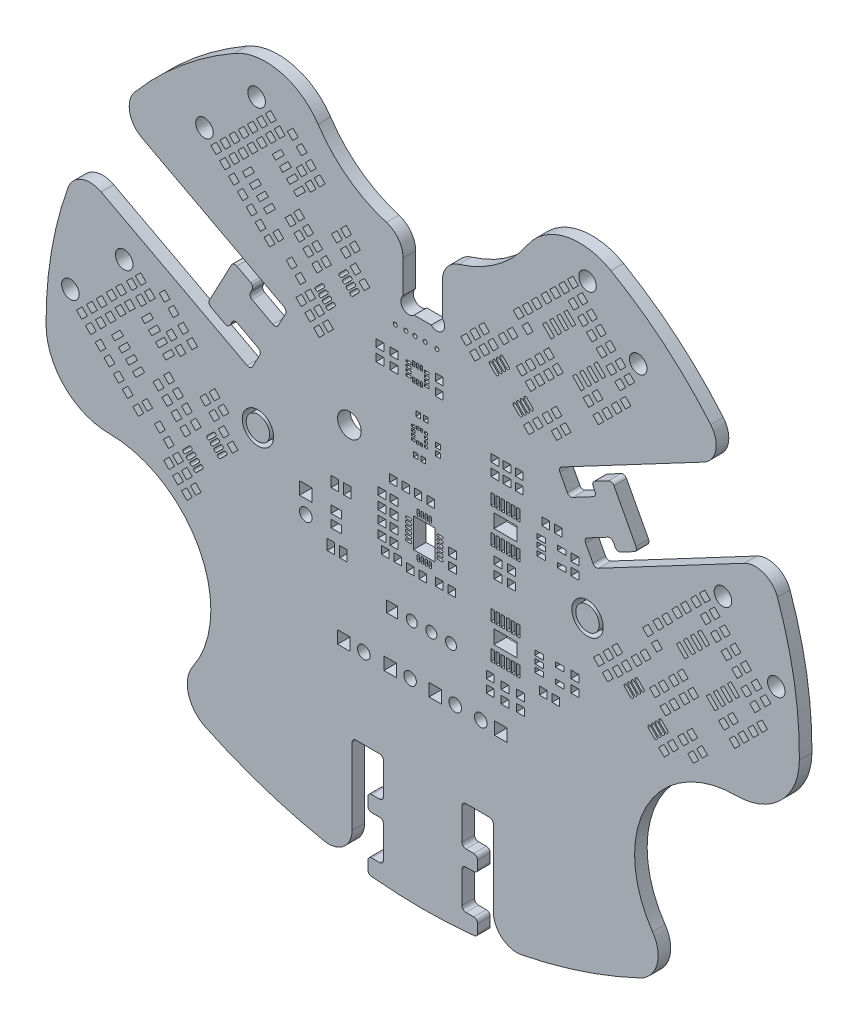
SolidWorks part; units mm, degrees
ref_plane "Plan de face" through (0, 0, 0) normal (0, 0, 1) x (1, 0, 0)
ref_plane "Plan de dessus" through (0, 0, 0) normal (0, 1, 0) x (1, 0, 0)
ref_plane "Plan de droite" through (0, 0, 0) normal (1, 0, 0) x (0, 0, -1)
sketch "Model" plane through (0, 0, 0) normal (0, 0, 1) x (1, 0, 0)
  line L0 (0.15, 36.75) -> (0.15, 36.45)
  line L1 (0.15, 36.45) -> (-0.25, 36.45)
  line L2 (-0.25, 36.45) -> (-0.25, 36.75)
  line L3 (-0.25, 36.75) -> (0.15, 36.75)
  line L4 (0.15, 37.25) -> (0.15, 36.95)
  line L5 (0.15, 36.95) -> (-0.25, 36.95)
  line L6 (-0.25, 36.95) -> (-0.25, 37.25)
  line L7 (-0.25, 37.25) -> (0.15, 37.25)
  line L8 (0.15, 37.75) -> (0.15, 37.45)
  line L9 (0.15, 37.45) -> (-0.25, 37.45)
  line L10 (-0.25, 37.45) -> (-0.25, 37.75)
  line L11 (-0.25, 37.75) -> (0.15, 37.75)
  line L12 (0.15, 38.25) -> (0.15, 37.95)
  line L13 (0.15, 37.95) -> (-0.25, 37.95)
  line L14 (-0.25, 37.95) -> (-0.25, 38.25)
  line L15 (-0.25, 38.25) -> (0.15, 38.25)
  line L16 (-0.75, 38.35) -> (-0.45, 38.35)
  line L17 (-0.45, 38.35) -> (-0.45, 37.95)
  line L18 (-0.45, 37.95) -> (-0.75, 37.95)
  line L19 (-0.75, 37.95) -> (-0.75, 38.35)
  line L20 (-1.25, 38.35) -> (-0.95, 38.35)
  line L21 (-0.95, 38.35) -> (-0.95, 37.95)
  line L22 (-0.95, 37.95) -> (-1.25, 37.95)
  line L23 (-1.25, 37.95) -> (-1.25, 38.35)
  line L24 (-1.45, 38.25) -> (-1.45, 37.95)
  line L25 (-1.45, 37.95) -> (-1.85, 37.95)
  line L26 (-1.85, 37.95) -> (-1.85, 38.25)
  line L27 (-1.85, 38.25) -> (-1.45, 38.25)
  line L28 (-1.45, 37.75) -> (-1.45, 37.45)
  line L29 (-1.45, 37.45) -> (-1.85, 37.45)
  line L30 (-1.85, 37.45) -> (-1.85, 37.75)
  line L31 (-1.85, 37.75) -> (-1.45, 37.75)
  line L32 (-1.45, 37.25) -> (-1.45, 36.95)
  line L33 (-1.45, 36.95) -> (-1.85, 36.95)
  line L34 (-1.85, 36.95) -> (-1.85, 37.25)
  line L35 (-1.85, 37.25) -> (-1.45, 37.25)
  line L36 (-1.45, 36.75) -> (-1.45, 36.45)
  line L37 (-1.45, 36.45) -> (-1.85, 36.45)
  line L38 (-1.85, 36.45) -> (-1.85, 36.75)
  line L39 (-1.85, 36.75) -> (-1.45, 36.75)
  line L40 (-1.25, 36.75) -> (-0.95, 36.75)
  line L41 (-0.95, 36.75) -> (-0.95, 36.35)
  line L42 (-0.95, 36.35) -> (-1.25, 36.35)
  line L43 (-1.25, 36.35) -> (-1.25, 36.75)
  line L44 (-0.75, 36.75) -> (-0.45, 36.75)
  line L45 (-0.45, 36.75) -> (-0.45, 36.35)
  line L46 (-0.45, 36.35) -> (-0.75, 36.35)
  line L47 (-0.75, 36.35) -> (-0.75, 36.75)
  line L48 (13.85, 20.55) -> (13.85, 21.15)
  line L49 (13.85, 21.15) -> (14.95, 21.15)
  line L50 (14.95, 21.15) -> (14.95, 20.55)
  line L51 (14.95, 20.55) -> (13.85, 20.55)
  line L52 (13.85, 19.6) -> (13.85, 20.2)
  line L53 (13.85, 20.2) -> (14.95, 20.2)
  line L54 (14.95, 20.2) -> (14.95, 19.6)
  line L55 (14.95, 19.6) -> (13.85, 19.6)
  line L56 (13.85, 18.65) -> (13.85, 19.25)
  line L57 (13.85, 19.25) -> (14.95, 19.25)
  line L58 (14.95, 19.25) -> (14.95, 18.65)
  line L59 (14.95, 18.65) -> (13.85, 18.65)
  line L60 (16.45, 18.65) -> (16.45, 19.25)
  line L61 (16.45, 19.25) -> (17.55, 19.25)
  line L62 (17.55, 19.25) -> (17.55, 18.65)
  line L63 (17.55, 18.65) -> (16.45, 18.65)
  line L64 (16.45, 20.55) -> (16.45, 21.15)
  line L65 (16.45, 21.15) -> (17.55, 21.15)
  line L66 (17.55, 21.15) -> (17.55, 20.55)
  line L67 (17.55, 20.55) -> (16.45, 20.55)
  line L68 (14.1, 33.55) -> (14.1, 34.15)
  line L69 (14.1, 34.15) -> (15.2, 34.15)
  line L70 (15.2, 34.15) -> (15.2, 33.55)
  line L71 (15.2, 33.55) -> (14.1, 33.55)
  line L72 (14.1, 32.6) -> (14.1, 33.2)
  line L73 (14.1, 33.2) -> (15.2, 33.2)
  line L74 (15.2, 33.2) -> (15.2, 32.6)
  line L75 (15.2, 32.6) -> (14.1, 32.6)
  line L76 (14.1, 31.65) -> (14.1, 32.25)
  line L77 (14.1, 32.25) -> (15.2, 32.25)
  line L78 (15.2, 32.25) -> (15.2, 31.65)
  line L79 (15.2, 31.65) -> (14.1, 31.65)
  line L80 (16.7, 31.65) -> (16.7, 32.25)
  line L81 (16.7, 32.25) -> (17.8, 32.25)
  line L82 (17.8, 32.25) -> (17.8, 31.65)
  line L83 (17.8, 31.65) -> (16.7, 31.65)
  line L84 (16.7, 33.55) -> (16.7, 34.15)
  line L85 (16.7, 34.15) -> (17.8, 34.15)
  line L86 (17.8, 34.15) -> (17.8, 33.55)
  line L87 (17.8, 33.55) -> (16.7, 33.55)
  line L88 (1.82, 36.815) -> (1.82, 36.225)
  line L89 (1.82, 36.225) -> (1.18, 36.225)
  line L90 (1.18, 36.225) -> (1.18, 36.815)
  line L91 (1.18, 36.815) -> (1.82, 36.815)
  line L92 (1.82, 37.775) -> (1.82, 37.185)
  line L93 (1.82, 37.185) -> (1.18, 37.185)
  line L94 (1.18, 37.185) -> (1.18, 37.775)
  line L95 (1.18, 37.775) -> (1.82, 37.775)
  line L96 (-0.665, 35.32) -> (-0.075, 35.32)
  line L97 (-0.075, 35.32) -> (-0.075, 34.68)
  line L98 (-0.075, 34.68) -> (-0.665, 34.68)
  line L99 (-0.665, 34.68) -> (-0.665, 35.32)
  line L100 (-1.625, 35.32) -> (-1.035, 35.32)
  line L101 (-1.035, 35.32) -> (-1.035, 34.68)
  line L102 (-1.035, 34.68) -> (-1.625, 34.68)
  line L103 (-1.625, 34.68) -> (-1.625, 35.32)
  line L104 (-0.365, 39.97) -> (0.225, 39.97)
  line L105 (0.225, 39.97) -> (0.225, 39.33)
  line L106 (0.225, 39.33) -> (-0.365, 39.33)
  line L107 (-0.365, 39.33) -> (-0.365, 39.97)
  line L108 (-1.325, 39.97) -> (-0.735, 39.97)
  line L109 (-0.735, 39.97) -> (-0.735, 39.33)
  line L110 (-0.735, 39.33) -> (-1.325, 39.33)
  line L111 (-1.325, 39.33) -> (-1.325, 39.97)
  line L112 (-10.525, 27.425) -> (-9.575, 27.425)
  line L113 (-9.575, 27.425) -> (-9.575, 26.075)
  line L114 (-9.575, 26.075) -> (-10.525, 26.075)
  line L115 (-10.525, 26.075) -> (-10.525, 27.425)
  line L116 (-12.125, 27.425) -> (-11.175, 27.425)
  line L117 (-11.175, 27.425) -> (-11.175, 26.075)
  line L118 (-11.175, 26.075) -> (-12.125, 26.075)
  line L119 (-12.125, 26.075) -> (-12.125, 27.425)
  line L120 (-11.025, 20.225) -> (-10.075, 20.225)
  line L121 (-10.075, 20.225) -> (-10.075, 18.875)
  line L122 (-10.075, 18.875) -> (-11.025, 18.875)
  line L123 (-11.025, 18.875) -> (-11.025, 20.225)
  line L124 (-12.625, 20.225) -> (-11.675, 20.225)
  line L125 (-11.675, 20.225) -> (-11.675, 18.875)
  line L126 (-11.675, 18.875) -> (-12.625, 18.875)
  line L127 (-12.625, 18.875) -> (-12.625, 20.225)
  line L128 (-12.125, 23.225) -> (-12.125, 24.175)
  line L129 (-12.125, 24.175) -> (-10.775, 24.175)
  line L130 (-10.775, 24.175) -> (-10.775, 23.225)
  line L131 (-10.775, 23.225) -> (-12.125, 23.225)
  line L132 (-12.125, 21.625) -> (-12.125, 22.575)
  line L133 (-12.125, 22.575) -> (-10.775, 22.575)
  line L134 (-10.775, 22.575) -> (-10.775, 21.625)
  line L135 (-10.775, 21.625) -> (-12.125, 21.625)
  line L136 (27.3989, 23.429) -> (26.6565, 24.1714)
  line L137 (26.9747, 24.4896) -> (27.7171, 23.7472)
  line L138 (26.9393, 22.9694) -> (26.1969, 23.7118)
  line L139 (26.5151, 24.03) -> (27.2575, 23.2876)
  line L140 (26.4797, 22.5098) -> (25.7373, 23.2522)
  line L141 (26.0555, 23.5704) -> (26.7979, 22.828)
  line L142 (26.0201, 22.0502) -> (25.2777, 22.7926)
  line L143 (25.5959, 23.1108) -> (26.3383, 22.3684)
  line L144 (29.0607, 19.0096) -> (28.3183, 19.752)
  line L145 (28.6365, 20.0702) -> (29.3789, 19.3278)
  line L146 (29.5203, 19.4692) -> (28.7779, 20.2116)
  line L147 (29.0961, 20.5298) -> (29.8385, 19.7874)
  line L148 (29.9799, 19.9288) -> (29.2375, 20.6712)
  line L149 (29.5557, 20.9894) -> (30.2981, 20.247)
  line L150 (30.4395, 20.3884) -> (29.6971, 21.1308)
  line L151 (30.0153, 21.449) -> (30.7577, 20.7066)
  line L152 (-29.8922, 21.3049) -> (-30.6346, 20.5625)
  line L153 (-30.9528, 20.8807) -> (-30.2104, 21.6231)
  line L154 (-29.4326, 20.8453) -> (-30.175, 20.1029)
  line L155 (-30.4932, 20.4211) -> (-29.7508, 21.1635)
  line L156 (-28.973, 20.3857) -> (-29.7154, 19.6433)
  line L157 (-30.0336, 19.9615) -> (-29.2912, 20.7039)
  line L158 (-28.5134, 19.9261) -> (-29.2558, 19.1837)
  line L159 (-29.574, 19.5019) -> (-28.8316, 20.2443)
  line L160 (-25.4728, 22.9667) -> (-26.2152, 22.2243)
  line L161 (-26.5334, 22.5425) -> (-25.791, 23.2849)
  line L162 (-25.9324, 23.4263) -> (-26.6748, 22.6839)
  line L163 (-26.993, 23.0021) -> (-26.2506, 23.7445)
  line L164 (-26.392, 23.8859) -> (-27.1344, 23.1435)
  line L165 (-27.4526, 23.4617) -> (-26.7102, 24.2041)
  line L166 (-26.8516, 24.3455) -> (-27.594, 23.6031)
  line L167 (-27.9122, 23.9213) -> (-27.1698, 24.6637)
  line L168 (10.2055, 50.428) -> (9.4631, 51.1704)
  line L169 (9.7813, 51.4886) -> (10.5237, 50.7462)
  line L170 (9.7459, 49.9684) -> (9.0035, 50.7108)
  line L171 (9.3217, 51.029) -> (10.0641, 50.2866)
  line L172 (9.2863, 49.5088) -> (8.5439, 50.2512)
  line L173 (8.8621, 50.5694) -> (9.6045, 49.827)
  line L174 (8.8267, 49.0492) -> (8.0843, 49.7916)
  line L175 (8.4025, 50.1098) -> (9.1449, 49.3674)
  line L176 (11.8673, 46.0086) -> (11.1249, 46.751)
  line L177 (11.4431, 47.0692) -> (12.1855, 46.3268)
  line L178 (12.3269, 46.4682) -> (11.5845, 47.2106)
  line L179 (11.9027, 47.5288) -> (12.6451, 46.7864)
  line L180 (12.7865, 46.9278) -> (12.0441, 47.6702)
  line L181 (12.3623, 47.9884) -> (13.1047, 47.246)
  line L182 (13.2461, 47.3874) -> (12.5037, 48.1298)
  line L183 (12.8219, 48.448) -> (13.5643, 47.7056)
  line L184 (-13.0317, 47.6509) -> (-13.7741, 46.9085)
  line L185 (-14.0923, 47.2267) -> (-13.3499, 47.9691)
  line L186 (-12.5721, 47.1913) -> (-13.3145, 46.4489)
  line L187 (-13.6327, 46.7671) -> (-12.8903, 47.5095)
  line L188 (-12.1125, 46.7317) -> (-12.8549, 45.9893)
  line L189 (-13.1731, 46.3075) -> (-12.4307, 47.0499)
  line L190 (-11.6529, 46.2721) -> (-12.3953, 45.5297)
  line L191 (-12.7135, 45.8479) -> (-11.9711, 46.5903)
  line L192 (-8.6123, 49.3127) -> (-9.3547, 48.5703)
  line L193 (-9.6729, 48.8885) -> (-8.9305, 49.6309)
  line L194 (-9.0719, 49.7723) -> (-9.8143, 49.0299)
  line L195 (-10.1325, 49.3481) -> (-9.3901, 50.0905)
  line L196 (-9.5315, 50.2319) -> (-10.2739, 49.4895)
  line L197 (-10.5921, 49.8077) -> (-9.8497, 50.5501)
  line L198 (-9.9911, 50.6915) -> (-10.7335, 49.9491)
  line L199 (-11.0517, 50.2673) -> (-10.3093, 51.0097)
  line L200 (37.2241, 26.3246) -> (36.7999, 25.9004)
  line L201 (36.7999, 25.9004) -> (35.7039, 26.9964)
  line L202 (35.7039, 26.9964) -> (36.1281, 27.4206)
  line L203 (36.1281, 27.4206) -> (37.2241, 26.3246)
  line L204 (38.1222, 27.2226) -> (37.698, 26.7984)
  line L205 (37.698, 26.7984) -> (36.602, 27.8944)
  line L206 (36.602, 27.8944) -> (37.0262, 28.3186)
  line L207 (37.0262, 28.3186) -> (38.1222, 27.2226)
  line L208 (39.0202, 28.1206) -> (38.596, 27.6964)
  line L209 (38.596, 27.6964) -> (37.5, 28.7924)
  line L210 (37.5, 28.7924) -> (37.9242, 29.2166)
  line L211 (37.9242, 29.2166) -> (39.0202, 28.1206)
  line L212 (39.9182, 29.0187) -> (39.494, 28.5945)
  line L213 (39.494, 28.5945) -> (38.398, 29.6905)
  line L214 (38.398, 29.6905) -> (38.8222, 30.1147)
  line L215 (38.8222, 30.1147) -> (39.9182, 29.0187)
  line L216 (36.0999, 32.837) -> (35.6757, 32.4128)
  line L217 (35.6757, 32.4128) -> (34.5797, 33.5088)
  line L218 (34.5797, 33.5088) -> (35.0039, 33.933)
  line L219 (35.0039, 33.933) -> (36.0999, 32.837)
  line L220 (35.2018, 31.939) -> (34.7776, 31.5148)
  line L221 (34.7776, 31.5148) -> (33.6816, 32.6108)
  line L222 (33.6816, 32.6108) -> (34.1058, 33.035)
  line L223 (34.1058, 33.035) -> (35.2018, 31.939)
  line L224 (34.3038, 31.041) -> (33.8796, 30.6168)
  line L225 (33.8796, 30.6168) -> (32.7836, 31.7128)
  line L226 (32.7836, 31.7128) -> (33.2078, 32.137)
  line L227 (33.2078, 32.137) -> (34.3038, 31.041)
  line L228 (33.4058, 30.1429) -> (32.9816, 29.7187)
  line L229 (32.9816, 29.7187) -> (31.8856, 30.8147)
  line L230 (31.8856, 30.8147) -> (32.3098, 31.2389)
  line L231 (32.3098, 31.2389) -> (33.4058, 30.1429)
  line L232 (-32.505, 31.1302) -> (-32.0808, 30.706)
  line L233 (-32.0808, 30.706) -> (-33.1768, 29.61)
  line L234 (-33.1768, 29.61) -> (-33.601, 30.0342)
  line L235 (-33.601, 30.0342) -> (-32.505, 31.1302)
  line L236 (-33.403, 32.0283) -> (-32.9788, 31.6041)
  line L237 (-32.9788, 31.6041) -> (-34.0748, 30.5081)
  line L238 (-34.0748, 30.5081) -> (-34.499, 30.9323)
  line L239 (-34.499, 30.9323) -> (-33.403, 32.0283)
  line L240 (-34.301, 32.9263) -> (-33.8768, 32.5021)
  line L241 (-33.8768, 32.5021) -> (-34.9728, 31.4061)
  line L242 (-34.9728, 31.4061) -> (-35.397, 31.8303)
  line L243 (-35.397, 31.8303) -> (-34.301, 32.9263)
  line L244 (-35.1991, 33.8243) -> (-34.7749, 33.4001)
  line L245 (-34.7749, 33.4001) -> (-35.8709, 32.3041)
  line L246 (-35.8709, 32.3041) -> (-36.2951, 32.7283)
  line L247 (-36.2951, 32.7283) -> (-35.1991, 33.8243)
  line L248 (-39.0174, 30.006) -> (-38.5932, 29.5818)
  line L249 (-38.5932, 29.5818) -> (-39.6892, 28.4858)
  line L250 (-39.6892, 28.4858) -> (-40.1134, 28.91)
  line L251 (-40.1134, 28.91) -> (-39.0174, 30.006)
  line L252 (-38.1194, 29.1079) -> (-37.6952, 28.6837)
  line L253 (-37.6952, 28.6837) -> (-38.7912, 27.5877)
  line L254 (-38.7912, 27.5877) -> (-39.2154, 28.0119)
  line L255 (-39.2154, 28.0119) -> (-38.1194, 29.1079)
  line L256 (-37.2214, 28.2099) -> (-36.7972, 27.7857)
  line L257 (-36.7972, 27.7857) -> (-37.8932, 26.6897)
  line L258 (-37.8932, 26.6897) -> (-38.3174, 27.1139)
  line L259 (-38.3174, 27.1139) -> (-37.2214, 28.2099)
  line L260 (-36.3233, 27.3119) -> (-35.8991, 26.8877)
  line L261 (-35.8991, 26.8877) -> (-36.9951, 25.7917)
  line L262 (-36.9951, 25.7917) -> (-37.4193, 26.2159)
  line L263 (-37.4193, 26.2159) -> (-36.3233, 27.3119)
  line L264 (20.1722, 53.1115) -> (19.748, 52.6873)
  line L265 (19.748, 52.6873) -> (18.652, 53.7833)
  line L266 (18.652, 53.7833) -> (19.0762, 54.2075)
  line L267 (19.0762, 54.2075) -> (20.1722, 53.1115)
  line L268 (21.0703, 54.0095) -> (20.6461, 53.5853)
  line L269 (20.6461, 53.5853) -> (19.5501, 54.6813)
  line L270 (19.5501, 54.6813) -> (19.9743, 55.1055)
  line L271 (19.9743, 55.1055) -> (21.0703, 54.0095)
  line L272 (21.9683, 54.9075) -> (21.5441, 54.4833)
  line L273 (21.5441, 54.4833) -> (20.4481, 55.5793)
  line L274 (20.4481, 55.5793) -> (20.8723, 56.0035)
  line L275 (20.8723, 56.0035) -> (21.9683, 54.9075)
  line L276 (22.8663, 55.8056) -> (22.4421, 55.3814)
  line L277 (22.4421, 55.3814) -> (21.3461, 56.4774)
  line L278 (21.3461, 56.4774) -> (21.7703, 56.9016)
  line L279 (21.7703, 56.9016) -> (22.8663, 55.8056)
  line L280 (19.048, 59.6239) -> (18.6238, 59.1997)
  line L281 (18.6238, 59.1997) -> (17.5278, 60.2957)
  line L282 (17.5278, 60.2957) -> (17.952, 60.7199)
  line L283 (17.952, 60.7199) -> (19.048, 59.6239)
  line L284 (18.1499, 58.7259) -> (17.7257, 58.3017)
  line L285 (17.7257, 58.3017) -> (16.6297, 59.3977)
  line L286 (16.6297, 59.3977) -> (17.0539, 59.8219)
  line L287 (17.0539, 59.8219) -> (18.1499, 58.7259)
  line L288 (17.2519, 57.8279) -> (16.8277, 57.4037)
  line L289 (16.8277, 57.4037) -> (15.7317, 58.4997)
  line L290 (15.7317, 58.4997) -> (16.1559, 58.9239)
  line L291 (16.1559, 58.9239) -> (17.2519, 57.8279)
  line L292 (16.3539, 56.9298) -> (15.9297, 56.5056)
  line L293 (15.9297, 56.5056) -> (14.8337, 57.6016)
  line L294 (14.8337, 57.6016) -> (15.2579, 58.0258)
  line L295 (15.2579, 58.0258) -> (16.3539, 56.9298)
  line L296 (-15.8213, 57.5115) -> (-15.3971, 57.0873)
  line L297 (-15.3971, 57.0873) -> (-16.4931, 55.9913)
  line L298 (-16.4931, 55.9913) -> (-16.9173, 56.4155)
  line L299 (-16.9173, 56.4155) -> (-15.8213, 57.5115)
  line L300 (-16.7193, 58.4096) -> (-16.2951, 57.9854)
  line L301 (-16.2951, 57.9854) -> (-17.3911, 56.8894)
  line L302 (-17.3911, 56.8894) -> (-17.8153, 57.3136)
  line L303 (-17.8153, 57.3136) -> (-16.7193, 58.4096)
  line L304 (-17.6173, 59.3076) -> (-17.1931, 58.8834)
  line L305 (-17.1931, 58.8834) -> (-18.2891, 57.7874)
  line L306 (-18.2891, 57.7874) -> (-18.7133, 58.2116)
  line L307 (-18.7133, 58.2116) -> (-17.6173, 59.3076)
  line L308 (-18.5154, 60.2056) -> (-18.0912, 59.7814)
  line L309 (-18.0912, 59.7814) -> (-19.1872, 58.6854)
  line L310 (-19.1872, 58.6854) -> (-19.6114, 59.1096)
  line L311 (-19.6114, 59.1096) -> (-18.5154, 60.2056)
  line L312 (-22.3337, 56.3873) -> (-21.9095, 55.9631)
  line L313 (-21.9095, 55.9631) -> (-23.0055, 54.8671)
  line L314 (-23.0055, 54.8671) -> (-23.4297, 55.2913)
  line L315 (-23.4297, 55.2913) -> (-22.3337, 56.3873)
  line L316 (-21.4357, 55.4892) -> (-21.0115, 55.065)
  line L317 (-21.0115, 55.065) -> (-22.1075, 53.969)
  line L318 (-22.1075, 53.969) -> (-22.5317, 54.3932)
  line L319 (-22.5317, 54.3932) -> (-21.4357, 55.4892)
  line L320 (-20.5377, 54.5912) -> (-20.1135, 54.167)
  line L321 (-20.1135, 54.167) -> (-21.2095, 53.071)
  line L322 (-21.2095, 53.071) -> (-21.6337, 53.4952)
  line L323 (-21.6337, 53.4952) -> (-20.5377, 54.5912)
  line L324 (-19.6396, 53.6932) -> (-19.2154, 53.269)
  line L325 (-19.2154, 53.269) -> (-20.3114, 52.173)
  line L326 (-20.3114, 52.173) -> (-20.7356, 52.5972)
  line L327 (-20.7356, 52.5972) -> (-19.6396, 53.6932)
  line L328 (1.5, 25.25) -> (2, 25.25)
  line L329 (2, 24.95) -> (1.5, 24.95)
  line L330 (1.5, 25.75) -> (2, 25.75)
  line L331 (2, 25.45) -> (1.5, 25.45)
  line L332 (1.5, 26.25) -> (2, 26.25)
  line L333 (2, 25.95) -> (1.5, 25.95)
  line L334 (1.5, 26.75) -> (2, 26.75)
  line L335 (2, 26.45) -> (1.5, 26.45)
  line L336 (1.5, 27.25) -> (2, 27.25)
  line L337 (2, 26.95) -> (1.5, 26.95)
  line L338 (1.5, 27.75) -> (2, 27.75)
  line L339 (2, 27.45) -> (1.5, 27.45)
  line L340 (0.35, 28.6) -> (0.35, 29.1)
  line L341 (0.65, 29.1) -> (0.65, 28.6)
  line L342 (-0.15, 28.6) -> (-0.15, 29.1)
  line L343 (0.15, 29.1) -> (0.15, 28.6)
  line L344 (-0.65, 28.6) -> (-0.65, 29.1)
  line L345 (-0.35, 29.1) -> (-0.35, 28.6)
  line L346 (-1.15, 28.6) -> (-1.15, 29.1)
  line L347 (-0.85, 29.1) -> (-0.85, 28.6)
  line L348 (-2.5, 27.75) -> (-2, 27.75)
  line L349 (-2, 27.45) -> (-2.5, 27.45)
  line L350 (-2.5, 27.25) -> (-2, 27.25)
  line L351 (-2, 26.95) -> (-2.5, 26.95)
  line L352 (-2.5, 26.75) -> (-2, 26.75)
  line L353 (-2, 26.45) -> (-2.5, 26.45)
  line L354 (-2.5, 26.25) -> (-2, 26.25)
  line L355 (-2, 25.95) -> (-2.5, 25.95)
  line L356 (-2.5, 25.75) -> (-2, 25.75)
  line L357 (-2, 25.45) -> (-2.5, 25.45)
  line L358 (-2.5, 25.25) -> (-2, 25.25)
  line L359 (-2, 24.95) -> (-2.5, 24.95)
  line L360 (-1.15, 23.6) -> (-1.15, 24.1)
  line L361 (-0.85, 24.1) -> (-0.85, 23.6)
  line L362 (-0.65, 23.6) -> (-0.65, 24.1)
  line L363 (-0.35, 24.1) -> (-0.35, 23.6)
  line L364 (-0.15, 23.6) -> (-0.15, 24.1)
  line L365 (0.15, 24.1) -> (0.15, 23.6)
  line L366 (0.35, 23.6) -> (0.35, 24.1)
  line L367 (0.65, 24.1) -> (0.65, 23.6)
  line L368 (1.125, 28.225) -> (1.125, 24.475)
  line L369 (1.125, 24.475) -> (-1.625, 24.475)
  line L370 (-1.625, 24.475) -> (-1.625, 28.225)
  line L371 (-1.625, 28.225) -> (1.125, 28.225)
  line L372 (8.7, 31.3005) -> (8.7, 29.8755)
  line L373 (8.7, 29.8755) -> (8.25, 29.8755)
  line L374 (8.25, 29.8755) -> (8.25, 31.3005)
  line L375 (8.25, 31.3005) -> (8.7, 31.3005)
  line L376 (9.35, 31.3005) -> (9.35, 29.8755)
  line L377 (9.35, 29.8755) -> (8.9, 29.8755)
  line L378 (8.9, 29.8755) -> (8.9, 31.3005)
  line L379 (8.9, 31.3005) -> (9.35, 31.3005)
  line L380 (10, 31.3005) -> (10, 29.8755)
  line L381 (10, 29.8755) -> (9.55, 29.8755)
  line L382 (9.55, 29.8755) -> (9.55, 31.3005)
  line L383 (9.55, 31.3005) -> (10, 31.3005)
  line L384 (10.65, 31.3005) -> (10.65, 29.8755)
  line L385 (10.65, 29.8755) -> (10.2, 29.8755)
  line L386 (10.2, 29.8755) -> (10.2, 31.3005)
  line L387 (10.2, 31.3005) -> (10.65, 31.3005)
  line L388 (11.3, 31.3005) -> (11.3, 29.8755)
  line L389 (11.3, 29.8755) -> (10.85, 29.8755)
  line L390 (10.85, 29.8755) -> (10.85, 31.3005)
  line L391 (10.85, 31.3005) -> (11.3, 31.3005)
  line L392 (11.95, 31.3005) -> (11.95, 29.8755)
  line L393 (11.95, 29.8755) -> (11.5, 29.8755)
  line L394 (11.5, 29.8755) -> (11.5, 31.3005)
  line L395 (11.5, 31.3005) -> (11.95, 31.3005)
  line L396 (11.95, 35.7245) -> (11.95, 34.2995)
  line L397 (11.95, 34.2995) -> (11.5, 34.2995)
  line L398 (11.5, 34.2995) -> (11.5, 35.7245)
  line L399 (11.5, 35.7245) -> (11.95, 35.7245)
  line L400 (11.3, 35.7245) -> (11.3, 34.2995)
  line L401 (11.3, 34.2995) -> (10.85, 34.2995)
  line L402 (10.85, 34.2995) -> (10.85, 35.7245)
  line L403 (10.85, 35.7245) -> (11.3, 35.7245)
  line L404 (10.65, 35.7245) -> (10.65, 34.2995)
  line L405 (10.65, 34.2995) -> (10.2, 34.2995)
  line L406 (10.2, 34.2995) -> (10.2, 35.7245)
  line L407 (10.2, 35.7245) -> (10.65, 35.7245)
  line L408 (10, 35.7245) -> (10, 34.2995)
  line L409 (10, 34.2995) -> (9.55, 34.2995)
  line L410 (9.55, 34.2995) -> (9.55, 35.7245)
  line L411 (9.55, 35.7245) -> (10, 35.7245)
  line L412 (9.35, 35.7245) -> (9.35, 34.2995)
  line L413 (9.35, 34.2995) -> (8.9, 34.2995)
  line L414 (8.9, 34.2995) -> (8.9, 35.7245)
  line L415 (8.9, 35.7245) -> (9.35, 35.7245)
  line L416 (8.7, 35.7245) -> (8.7, 34.2995)
  line L417 (8.7, 34.2995) -> (8.25, 34.2995)
  line L418 (8.25, 34.2995) -> (8.25, 35.7245)
  line L419 (8.25, 35.7245) -> (8.7, 35.7245)
  line L420 (8.6265, 33.6765) -> (11.5735, 33.6765)
  line L421 (11.5735, 33.6765) -> (11.5735, 31.9235)
  line L422 (11.5735, 31.9235) -> (8.6265, 31.9235)
  line L423 (8.6265, 31.9235) -> (8.6265, 33.6765)
  line L424 (11.5, 21.4995) -> (11.5, 22.9245)
  line L425 (11.5, 22.9245) -> (11.95, 22.9245)
  line L426 (11.95, 22.9245) -> (11.95, 21.4995)
  line L427 (11.95, 21.4995) -> (11.5, 21.4995)
  line L428 (10.85, 21.4995) -> (10.85, 22.9245)
  line L429 (10.85, 22.9245) -> (11.3, 22.9245)
  line L430 (11.3, 22.9245) -> (11.3, 21.4995)
  line L431 (11.3, 21.4995) -> (10.85, 21.4995)
  line L432 (10.2, 21.4995) -> (10.2, 22.9245)
  line L433 (10.2, 22.9245) -> (10.65, 22.9245)
  line L434 (10.65, 22.9245) -> (10.65, 21.4995)
  line L435 (10.65, 21.4995) -> (10.2, 21.4995)
  line L436 (9.55, 21.4995) -> (9.55, 22.9245)
  line L437 (9.55, 22.9245) -> (10, 22.9245)
  line L438 (10, 22.9245) -> (10, 21.4995)
  line L439 (10, 21.4995) -> (9.55, 21.4995)
  line L440 (8.9, 21.4995) -> (8.9, 22.9245)
  line L441 (8.9, 22.9245) -> (9.35, 22.9245)
  line L442 (9.35, 22.9245) -> (9.35, 21.4995)
  line L443 (9.35, 21.4995) -> (8.9, 21.4995)
  line L444 (8.25, 21.4995) -> (8.25, 22.9245)
  line L445 (8.25, 22.9245) -> (8.7, 22.9245)
  line L446 (8.7, 22.9245) -> (8.7, 21.4995)
  line L447 (8.7, 21.4995) -> (8.25, 21.4995)
  line L448 (8.25, 17.0755) -> (8.25, 18.5005)
  line L449 (8.25, 18.5005) -> (8.7, 18.5005)
  line L450 (8.7, 18.5005) -> (8.7, 17.0755)
  line L451 (8.7, 17.0755) -> (8.25, 17.0755)
  line L452 (8.9, 17.0755) -> (8.9, 18.5005)
  line L453 (8.9, 18.5005) -> (9.35, 18.5005)
  line L454 (9.35, 18.5005) -> (9.35, 17.0755)
  line L455 (9.35, 17.0755) -> (8.9, 17.0755)
  line L456 (9.55, 17.0755) -> (9.55, 18.5005)
  line L457 (9.55, 18.5005) -> (10, 18.5005)
  line L458 (10, 18.5005) -> (10, 17.0755)
  line L459 (10, 17.0755) -> (9.55, 17.0755)
  line L460 (10.2, 17.0755) -> (10.2, 18.5005)
  line L461 (10.2, 18.5005) -> (10.65, 18.5005)
  line L462 (10.65, 18.5005) -> (10.65, 17.0755)
  line L463 (10.65, 17.0755) -> (10.2, 17.0755)
  line L464 (10.85, 17.0755) -> (10.85, 18.5005)
  line L465 (10.85, 18.5005) -> (11.3, 18.5005)
  line L466 (11.3, 18.5005) -> (11.3, 17.0755)
  line L467 (11.3, 17.0755) -> (10.85, 17.0755)
  line L468 (11.5, 17.0755) -> (11.5, 18.5005)
  line L469 (11.5, 18.5005) -> (11.95, 18.5005)
  line L470 (11.95, 18.5005) -> (11.95, 17.0755)
  line L471 (11.95, 17.0755) -> (11.5, 17.0755)
  line L472 (11.5735, 19.1235) -> (8.6265, 19.1235)
  line L473 (8.6265, 19.1235) -> (8.6265, 20.8765)
  line L474 (8.6265, 20.8765) -> (11.5735, 20.8765)
  line L475 (11.5735, 20.8765) -> (11.5735, 19.1235)
  line L476 (0.35, 43.5) -> (0.35, 43.2)
  line L477 (0.35, 43.2) -> (-0.25, 43.2)
  line L478 (-0.25, 43.2) -> (-0.25, 43.5)
  line L479 (-0.25, 43.5) -> (0.35, 43.5)
  line L480 (0.35, 44) -> (0.35, 43.7)
  line L481 (0.35, 43.7) -> (-0.25, 43.7)
  line L482 (-0.25, 43.7) -> (-0.25, 44)
  line L483 (-0.25, 44) -> (0.35, 44)
  line L484 (0.35, 44.5) -> (0.35, 44.2)
  line L485 (0.35, 44.2) -> (-0.25, 44.2)
  line L486 (-0.25, 44.2) -> (-0.25, 44.5)
  line L487 (-0.25, 44.5) -> (0.35, 44.5)
  line L488 (0.35, 45) -> (0.35, 44.7)
  line L489 (0.35, 44.7) -> (-0.25, 44.7)
  line L490 (-0.25, 44.7) -> (-0.25, 45)
  line L491 (-0.25, 45) -> (0.35, 45)
  line L492 (-0.75, 45.3) -> (-0.45, 45.3)
  line L493 (-0.45, 45.3) -> (-0.45, 44.7)
  line L494 (-0.45, 44.7) -> (-0.75, 44.7)
  line L495 (-0.75, 44.7) -> (-0.75, 45.3)
  line L496 (-1.25, 45.3) -> (-0.95, 45.3)
  line L497 (-0.95, 45.3) -> (-0.95, 44.7)
  line L498 (-0.95, 44.7) -> (-1.25, 44.7)
  line L499 (-1.25, 44.7) -> (-1.25, 45.3)
  line L500 (-1.75, 45.3) -> (-1.45, 45.3)
  line L501 (-1.45, 45.3) -> (-1.45, 44.7)
  line L502 (-1.45, 44.7) -> (-1.75, 44.7)
  line L503 (-1.75, 44.7) -> (-1.75, 45.3)
  line L504 (-1.95, 45) -> (-1.95, 44.7)
  line L505 (-1.95, 44.7) -> (-2.55, 44.7)
  line L506 (-2.55, 44.7) -> (-2.55, 45)
  line L507 (-2.55, 45) -> (-1.95, 45)
  line L508 (-1.95, 44.5) -> (-1.95, 44.2)
  line L509 (-1.95, 44.2) -> (-2.55, 44.2)
  line L510 (-2.55, 44.2) -> (-2.55, 44.5)
  line L511 (-2.55, 44.5) -> (-1.95, 44.5)
  line L512 (-1.95, 44) -> (-1.95, 43.7)
  line L513 (-1.95, 43.7) -> (-2.55, 43.7)
  line L514 (-2.55, 43.7) -> (-2.55, 44)
  line L515 (-2.55, 44) -> (-1.95, 44)
  line L516 (-1.95, 43.5) -> (-1.95, 43.2)
  line L517 (-1.95, 43.2) -> (-2.55, 43.2)
  line L518 (-2.55, 43.2) -> (-2.55, 43.5)
  line L519 (-2.55, 43.5) -> (-1.95, 43.5)
  line L520 (-1.75, 43.5) -> (-1.45, 43.5)
  line L521 (-1.45, 43.5) -> (-1.45, 42.9)
  line L522 (-1.45, 42.9) -> (-1.75, 42.9)
  line L523 (-1.75, 42.9) -> (-1.75, 43.5)
  line L524 (-1.25, 43.5) -> (-0.95, 43.5)
  line L525 (-0.95, 43.5) -> (-0.95, 42.9)
  line L526 (-0.95, 42.9) -> (-1.25, 42.9)
  line L527 (-1.25, 42.9) -> (-1.25, 43.5)
  line L528 (-0.75, 43.5) -> (-0.45, 43.5)
  line L529 (-0.45, 43.5) -> (-0.45, 42.9)
  line L530 (-0.45, 42.9) -> (-0.75, 42.9)
  line L531 (-0.75, 42.9) -> (-0.75, 43.5)
  line L532 (15.375, 16.45) -> (14.425, 16.45)
  line L533 (14.425, 16.45) -> (14.425, 17.45)
  line L534 (14.425, 17.45) -> (15.375, 17.45)
  line L535 (15.375, 17.45) -> (15.375, 16.45)
  line L536 (16.975, 16.45) -> (16.025, 16.45)
  line L537 (16.025, 16.45) -> (16.025, 17.45)
  line L538 (16.025, 17.45) -> (16.975, 17.45)
  line L539 (16.975, 17.45) -> (16.975, 16.45)
  line L540 (15.675, 35.3) -> (14.725, 35.3)
  line L541 (14.725, 35.3) -> (14.725, 36.3)
  line L542 (14.725, 36.3) -> (15.675, 36.3)
  line L543 (15.675, 36.3) -> (15.675, 35.3)
  line L544 (17.275, 35.3) -> (16.325, 35.3)
  line L545 (16.325, 35.3) -> (16.325, 36.3)
  line L546 (16.325, 36.3) -> (17.275, 36.3)
  line L547 (17.275, 36.3) -> (17.275, 35.3)
  line L548 (18.45, 20.275) -> (18.45, 21.225)
  line L549 (18.45, 21.225) -> (19.45, 21.225)
  line L550 (19.45, 21.225) -> (19.45, 20.275)
  line L551 (19.45, 20.275) -> (18.45, 20.275)
  line L552 (18.45, 18.675) -> (18.45, 19.625)
  line L553 (18.45, 19.625) -> (19.45, 19.625)
  line L554 (19.45, 19.625) -> (19.45, 18.675)
  line L555 (19.45, 18.675) -> (18.45, 18.675)
  line L556 (18.45, 33.225) -> (18.45, 34.175)
  line L557 (18.45, 34.175) -> (19.45, 34.175)
  line L558 (19.45, 34.175) -> (19.45, 33.225)
  line L559 (19.45, 33.225) -> (18.45, 33.225)
  line L560 (18.45, 31.625) -> (18.45, 32.575)
  line L561 (18.45, 32.575) -> (19.45, 32.575)
  line L562 (19.45, 32.575) -> (19.45, 31.625)
  line L563 (19.45, 31.625) -> (18.45, 31.625)
  line L564 (27.2576, 27.6363) -> (27.9293, 28.308)
  line L565 (27.9293, 28.308) -> (28.6364, 27.6009)
  line L566 (28.6364, 27.6009) -> (27.9647, 26.9292)
  line L567 (27.9647, 26.9292) -> (27.2576, 27.6363)
  line L568 (26.1262, 26.5049) -> (26.7979, 27.1766)
  line L569 (26.7979, 27.1766) -> (27.505, 26.4695)
  line L570 (27.505, 26.4695) -> (26.8333, 25.7978)
  line L571 (26.8333, 25.7978) -> (26.1262, 26.5049)
  line L572 (32.4194, 35.4852) -> (33.0911, 36.1569)
  line L573 (33.0911, 36.1569) -> (33.7982, 35.4498)
  line L574 (33.7982, 35.4498) -> (33.1265, 34.7781)
  line L575 (33.1265, 34.7781) -> (32.4194, 35.4852)
  line L576 (31.288, 34.3538) -> (31.9597, 35.0255)
  line L577 (31.9597, 35.0255) -> (32.6668, 34.3184)
  line L578 (32.6668, 34.3184) -> (31.9951, 33.6467)
  line L579 (31.9951, 33.6467) -> (31.288, 34.3538)
  line L580 (38.7127, 34.0003) -> (39.3844, 34.672)
  line L581 (39.3844, 34.672) -> (40.0915, 33.9649)
  line L582 (40.0915, 33.9649) -> (39.4198, 33.2932)
  line L583 (39.4198, 33.2932) -> (38.7127, 34.0003)
  line L584 (37.5813, 32.8689) -> (38.253, 33.5406)
  line L585 (38.253, 33.5406) -> (38.9601, 32.8335)
  line L586 (38.9601, 32.8335) -> (38.2884, 32.1618)
  line L587 (38.2884, 32.1618) -> (37.5813, 32.8689)
  line L588 (30.0153, 33.0104) -> (30.687, 33.6821)
  line L589 (30.687, 33.6821) -> (31.3941, 32.975)
  line L590 (31.3941, 32.975) -> (30.7224, 32.3033)
  line L591 (30.7224, 32.3033) -> (30.0153, 33.0104)
  line L592 (28.8839, 31.879) -> (29.5556, 32.5507)
  line L593 (29.5556, 32.5507) -> (30.2627, 31.8436)
  line L594 (30.2627, 31.8436) -> (29.591, 31.1719)
  line L595 (29.591, 31.1719) -> (28.8839, 31.879)
  line L596 (29.591, 25.3736) -> (30.2627, 26.0453)
  line L597 (30.2627, 26.0453) -> (30.9698, 25.3382)
  line L598 (30.9698, 25.3382) -> (30.2981, 24.6665)
  line L599 (30.2981, 24.6665) -> (29.591, 25.3736)
  line L600 (28.4596, 24.2422) -> (29.1313, 24.9139)
  line L601 (29.1313, 24.9139) -> (29.8384, 24.2068)
  line L602 (29.8384, 24.2068) -> (29.1667, 23.5351)
  line L603 (29.1667, 23.5351) -> (28.4596, 24.2422)
  line L604 (37.3692, 35.3438) -> (38.0409, 36.0155)
  line L605 (38.0409, 36.0155) -> (38.748, 35.3084)
  line L606 (38.748, 35.3084) -> (38.0763, 34.6367)
  line L607 (38.0763, 34.6367) -> (37.3692, 35.3438)
  line L608 (36.2378, 34.2124) -> (36.9095, 34.8841)
  line L609 (36.9095, 34.8841) -> (37.6166, 34.177)
  line L610 (37.6166, 34.177) -> (36.9449, 33.5053)
  line L611 (36.9449, 33.5053) -> (36.2378, 34.2124)
  line L612 (30.9345, 24.0301) -> (31.6062, 24.7018)
  line L613 (31.6062, 24.7018) -> (32.3133, 23.9947)
  line L614 (32.3133, 23.9947) -> (31.6416, 23.323)
  line L615 (31.6416, 23.323) -> (30.9345, 24.0301)
  line L616 (29.8031, 22.8987) -> (30.4748, 23.5704)
  line L617 (30.4748, 23.5704) -> (31.1819, 22.8633)
  line L618 (31.1819, 22.8633) -> (30.5102, 22.1916)
  line L619 (30.5102, 22.1916) -> (29.8031, 22.8987)
  line L620 (40.0562, 32.7275) -> (40.7279, 33.3992)
  line L621 (40.7279, 33.3992) -> (41.435, 32.6921)
  line L622 (41.435, 32.6921) -> (40.7633, 32.0204)
  line L623 (40.7633, 32.0204) -> (40.0562, 32.7275)
  line L624 (38.9248, 31.5961) -> (39.5965, 32.2678)
  line L625 (39.5965, 32.2678) -> (40.3036, 31.5607)
  line L626 (40.3036, 31.5607) -> (39.6319, 30.889)
  line L627 (39.6319, 30.889) -> (38.9248, 31.5961)
  line L628 (36.061, 36.652) -> (36.7327, 37.3237)
  line L629 (36.7327, 37.3237) -> (37.4398, 36.6166)
  line L630 (37.4398, 36.6166) -> (36.7681, 35.9449)
  line L631 (36.7681, 35.9449) -> (36.061, 36.652)
  line L632 (34.9296, 35.5206) -> (35.6013, 36.1923)
  line L633 (35.6013, 36.1923) -> (36.3084, 35.4852)
  line L634 (36.3084, 35.4852) -> (35.6367, 34.8135)
  line L635 (35.6367, 34.8135) -> (34.9296, 35.5206)
  line L636 (40.7632, 29.3688) -> (40.0915, 30.0405)
  line L637 (40.0915, 30.0405) -> (40.7986, 30.7476)
  line L638 (40.7986, 30.7476) -> (41.4703, 30.0759)
  line L639 (41.4703, 30.0759) -> (40.7632, 29.3688)
  line L640 (41.8946, 28.2374) -> (41.2229, 28.9091)
  line L641 (41.2229, 28.9091) -> (41.93, 29.6162)
  line L642 (41.93, 29.6162) -> (42.6017, 28.9445)
  line L643 (42.6017, 28.9445) -> (41.8946, 28.2374)
  line L644 (28.2474, 29.793) -> (27.5757, 30.4647)
  line L645 (27.5757, 30.4647) -> (28.2828, 31.1718)
  line L646 (28.2828, 31.1718) -> (28.9545, 30.5001)
  line L647 (28.9545, 30.5001) -> (28.2474, 29.793)
  line L648 (29.3788, 28.6616) -> (28.7071, 29.3333)
  line L649 (28.7071, 29.3333) -> (29.4142, 30.0404)
  line L650 (29.4142, 30.0404) -> (30.0859, 29.3687)
  line L651 (30.0859, 29.3687) -> (29.3788, 28.6616)
  line L652 (33.1973, 21.8381) -> (33.869, 22.5098)
  line L653 (33.869, 22.5098) -> (34.5761, 21.8027)
  line L654 (34.5761, 21.8027) -> (33.9044, 21.131)
  line L655 (33.9044, 21.131) -> (33.1973, 21.8381)
  line L656 (32.0659, 20.7067) -> (32.7376, 21.3784)
  line L657 (32.7376, 21.3784) -> (33.4447, 20.6713)
  line L658 (33.4447, 20.6713) -> (32.773, 19.9996)
  line L659 (32.773, 19.9996) -> (32.0659, 20.7067)
  line L660 (34.4701, 20.5653) -> (35.1418, 21.237)
  line L661 (35.1418, 21.237) -> (35.8489, 20.5299)
  line L662 (35.8489, 20.5299) -> (35.1772, 19.8582)
  line L663 (35.1772, 19.8582) -> (34.4701, 20.5653)
  line L664 (33.3387, 19.4339) -> (34.0104, 20.1056)
  line L665 (34.0104, 20.1056) -> (34.7175, 19.3985)
  line L666 (34.7175, 19.3985) -> (34.0458, 18.7268)
  line L667 (34.0458, 18.7268) -> (33.3387, 19.4339)
  line L668 (39.738, 24.8433) -> (40.4097, 25.515)
  line L669 (40.4097, 25.515) -> (41.1168, 24.8079)
  line L670 (41.1168, 24.8079) -> (40.4451, 24.1362)
  line L671 (40.4451, 24.1362) -> (39.738, 24.8433)
  line L672 (38.6066, 23.7119) -> (39.2783, 24.3836)
  line L673 (39.2783, 24.3836) -> (39.9854, 23.6765)
  line L674 (39.9854, 23.6765) -> (39.3137, 23.0048)
  line L675 (39.3137, 23.0048) -> (38.6066, 23.7119)
  line L676 (38.3945, 26.1868) -> (39.0662, 26.8585)
  line L677 (39.0662, 26.8585) -> (39.7733, 26.1514)
  line L678 (39.7733, 26.1514) -> (39.1016, 25.4797)
  line L679 (39.1016, 25.4797) -> (38.3945, 26.1868)
  line L680 (37.2631, 25.0554) -> (37.9348, 25.7271)
  line L681 (37.9348, 25.7271) -> (38.6419, 25.02)
  line L682 (38.6419, 25.02) -> (37.9702, 24.3483)
  line L683 (37.9702, 24.3483) -> (37.2631, 25.0554)
  line L684 (-33.9581, 21.1636) -> (-34.6298, 21.8353)
  line L685 (-34.6298, 21.8353) -> (-33.9227, 22.5424)
  line L686 (-33.9227, 22.5424) -> (-33.251, 21.8707)
  line L687 (-33.251, 21.8707) -> (-33.9581, 21.1636)
  line L688 (-32.8267, 20.0322) -> (-33.4984, 20.7039)
  line L689 (-33.4984, 20.7039) -> (-32.7913, 21.411)
  line L690 (-32.7913, 21.411) -> (-32.1196, 20.7393)
  line L691 (-32.1196, 20.7393) -> (-32.8267, 20.0322)
  line L692 (-41.5241, 26.3962) -> (-42.1958, 27.0679)
  line L693 (-42.1958, 27.0679) -> (-41.4887, 27.775)
  line L694 (-41.4887, 27.775) -> (-40.817, 27.1033)
  line L695 (-40.817, 27.1033) -> (-41.5241, 26.3962)
  line L696 (-40.3927, 25.2648) -> (-41.0644, 25.9365)
  line L697 (-41.0644, 25.9365) -> (-40.3573, 26.6436)
  line L698 (-40.3573, 26.6436) -> (-39.6856, 25.9719)
  line L699 (-39.6856, 25.9719) -> (-40.3927, 25.2648)
  line L700 (-40.1099, 32.6188) -> (-40.7816, 33.2905)
  line L701 (-40.7816, 33.2905) -> (-40.0745, 33.9976)
  line L702 (-40.0745, 33.9976) -> (-39.4028, 33.3259)
  line L703 (-39.4028, 33.3259) -> (-40.1099, 32.6188)
  line L704 (-38.9785, 31.4874) -> (-39.6502, 32.1591)
  line L705 (-39.6502, 32.1591) -> (-38.9431, 32.8662)
  line L706 (-38.9431, 32.8662) -> (-38.2714, 32.1945)
  line L707 (-38.2714, 32.1945) -> (-38.9785, 31.4874)
  line L708 (-39.1907, 24.0628) -> (-39.8624, 24.7345)
  line L709 (-39.8624, 24.7345) -> (-39.1553, 25.4416)
  line L710 (-39.1553, 25.4416) -> (-38.4836, 24.7699)
  line L711 (-38.4836, 24.7699) -> (-39.1907, 24.0628)
  line L712 (-38.0593, 22.9314) -> (-38.731, 23.6031)
  line L713 (-38.731, 23.6031) -> (-38.0239, 24.3102)
  line L714 (-38.0239, 24.3102) -> (-37.3522, 23.6385)
  line L715 (-37.3522, 23.6385) -> (-38.0593, 22.9314)
  line L716 (-31.8514, 23.491) -> (-32.5231, 24.1627)
  line L717 (-32.5231, 24.1627) -> (-31.816, 24.8698)
  line L718 (-31.816, 24.8698) -> (-31.1443, 24.1981)
  line L719 (-31.1443, 24.1981) -> (-31.8514, 23.491)
  line L720 (-30.72, 22.3596) -> (-31.3917, 23.0313)
  line L721 (-31.3917, 23.0313) -> (-30.6846, 23.7384)
  line L722 (-30.6846, 23.7384) -> (-30.0129, 23.0667)
  line L723 (-30.0129, 23.0667) -> (-30.72, 22.3596)
  line L724 (-41.3827, 31.2753) -> (-42.0544, 31.947)
  line L725 (-42.0544, 31.947) -> (-41.3473, 32.6541)
  line L726 (-41.3473, 32.6541) -> (-40.6756, 31.9824)
  line L727 (-40.6756, 31.9824) -> (-41.3827, 31.2753)
  line L728 (-40.2513, 30.1439) -> (-40.923, 30.8156)
  line L729 (-40.923, 30.8156) -> (-40.2159, 31.5227)
  line L730 (-40.2159, 31.5227) -> (-39.5442, 30.851)
  line L731 (-39.5442, 30.851) -> (-40.2513, 30.1439)
  line L732 (-30.5226, 24.8699) -> (-31.1943, 25.5416)
  line L733 (-31.1943, 25.5416) -> (-30.4872, 26.2487)
  line L734 (-30.4872, 26.2487) -> (-29.8155, 25.577)
  line L735 (-29.8155, 25.577) -> (-30.5226, 24.8699)
  line L736 (-29.3912, 23.7385) -> (-30.0629, 24.4102)
  line L737 (-30.0629, 24.4102) -> (-29.3558, 25.1173)
  line L738 (-29.3558, 25.1173) -> (-28.6841, 24.4456)
  line L739 (-28.6841, 24.4456) -> (-29.3912, 23.7385)
  line L740 (-38.9078, 33.8208) -> (-39.5795, 34.4925)
  line L741 (-39.5795, 34.4925) -> (-38.8724, 35.1996)
  line L742 (-38.8724, 35.1996) -> (-38.2007, 34.5279)
  line L743 (-38.2007, 34.5279) -> (-38.9078, 33.8208)
  line L744 (-37.7764, 32.6894) -> (-38.4481, 33.3611)
  line L745 (-38.4481, 33.3611) -> (-37.741, 34.0682)
  line L746 (-37.741, 34.0682) -> (-37.0693, 33.3965)
  line L747 (-37.0693, 33.3965) -> (-37.7764, 32.6894)
  line L748 (-42.6202, 30.0378) -> (-43.2919, 30.7095)
  line L749 (-43.2919, 30.7095) -> (-42.5848, 31.4166)
  line L750 (-42.5848, 31.4166) -> (-41.9131, 30.7449)
  line L751 (-41.9131, 30.7449) -> (-42.6202, 30.0378)
  line L752 (-41.4888, 28.9064) -> (-42.1605, 29.5781)
  line L753 (-42.1605, 29.5781) -> (-41.4534, 30.2852)
  line L754 (-41.4534, 30.2852) -> (-40.7817, 29.6135)
  line L755 (-40.7817, 29.6135) -> (-41.4888, 28.9064)
  line L756 (-35.6552, 34.6339) -> (-36.3269, 33.9622)
  line L757 (-36.3269, 33.9622) -> (-37.034, 34.6693)
  line L758 (-37.034, 34.6693) -> (-36.3623, 35.341)
  line L759 (-36.3623, 35.341) -> (-35.6552, 34.6339)
  line L760 (-34.5238, 35.7653) -> (-35.1955, 35.0936)
  line L761 (-35.1955, 35.0936) -> (-35.9026, 35.8007)
  line L762 (-35.9026, 35.8007) -> (-35.2309, 36.4724)
  line L763 (-35.2309, 36.4724) -> (-34.5238, 35.7653)
  line L764 (-36.0087, 22.3303) -> (-36.6804, 21.6586)
  line L765 (-36.6804, 21.6586) -> (-37.3875, 22.3657)
  line L766 (-37.3875, 22.3657) -> (-36.7158, 23.0374)
  line L767 (-36.7158, 23.0374) -> (-36.0087, 22.3303)
  line L768 (-34.8773, 23.4617) -> (-35.549, 22.79)
  line L769 (-35.549, 22.79) -> (-36.2561, 23.4971)
  line L770 (-36.2561, 23.4971) -> (-35.5844, 24.1688)
  line L771 (-35.5844, 24.1688) -> (-34.8773, 23.4617)
  line L772 (-28.1598, 27.0326) -> (-28.8315, 27.7043)
  line L773 (-28.8315, 27.7043) -> (-28.1244, 28.4114)
  line L774 (-28.1244, 28.4114) -> (-27.4527, 27.7397)
  line L775 (-27.4527, 27.7397) -> (-28.1598, 27.0326)
  line L776 (-27.0284, 25.9012) -> (-27.7001, 26.5729)
  line L777 (-27.7001, 26.5729) -> (-26.993, 27.28)
  line L778 (-26.993, 27.28) -> (-26.3213, 26.6083)
  line L779 (-26.3213, 26.6083) -> (-27.0284, 25.9012)
  line L780 (-26.9931, 28.1993) -> (-27.6648, 28.871)
  line L781 (-27.6648, 28.871) -> (-26.9577, 29.5781)
  line L782 (-26.9577, 29.5781) -> (-26.286, 28.9064)
  line L783 (-26.286, 28.9064) -> (-26.9931, 28.1993)
  line L784 (-25.8617, 27.0679) -> (-26.5334, 27.7396)
  line L785 (-26.5334, 27.7396) -> (-25.8263, 28.4467)
  line L786 (-25.8263, 28.4467) -> (-25.1546, 27.775)
  line L787 (-25.1546, 27.775) -> (-25.8617, 27.0679)
  line L788 (-30.9882, 33.538) -> (-31.6599, 34.2097)
  line L789 (-31.6599, 34.2097) -> (-30.9528, 34.9168)
  line L790 (-30.9528, 34.9168) -> (-30.2811, 34.2451)
  line L791 (-30.2811, 34.2451) -> (-30.9882, 33.538)
  line L792 (-29.8568, 32.4066) -> (-30.5285, 33.0783)
  line L793 (-30.5285, 33.0783) -> (-29.8214, 33.7854)
  line L794 (-29.8214, 33.7854) -> (-29.1497, 33.1137)
  line L795 (-29.1497, 33.1137) -> (-29.8568, 32.4066)
  line L796 (-32.4732, 32.0531) -> (-33.1449, 32.7248)
  line L797 (-33.1449, 32.7248) -> (-32.4378, 33.4319)
  line L798 (-32.4378, 33.4319) -> (-31.7661, 32.7602)
  line L799 (-31.7661, 32.7602) -> (-32.4732, 32.0531)
  line L800 (-31.3418, 30.9217) -> (-32.0135, 31.5934)
  line L801 (-32.0135, 31.5934) -> (-31.3064, 32.3005)
  line L802 (-31.3064, 32.3005) -> (-30.6347, 31.6288)
  line L803 (-30.6347, 31.6288) -> (-31.3418, 30.9217)
  line L804 (10.3117, 54.6707) -> (10.9834, 55.3424)
  line L805 (10.9834, 55.3424) -> (11.6905, 54.6353)
  line L806 (11.6905, 54.6353) -> (11.0188, 53.9636)
  line L807 (11.0188, 53.9636) -> (10.3117, 54.6707)
  line L808 (9.1803, 53.5393) -> (9.852, 54.211)
  line L809 (9.852, 54.211) -> (10.5591, 53.5039)
  line L810 (10.5591, 53.5039) -> (9.8874, 52.8322)
  line L811 (9.8874, 52.8322) -> (9.1803, 53.5393)
  line L812 (15.7565, 61.8831) -> (16.4282, 62.5548)
  line L813 (16.4282, 62.5548) -> (17.1353, 61.8477)
  line L814 (17.1353, 61.8477) -> (16.4636, 61.176)
  line L815 (16.4636, 61.176) -> (15.7565, 61.8831)
  line L816 (14.6251, 60.7517) -> (15.2968, 61.4234)
  line L817 (15.2968, 61.4234) -> (16.0039, 60.7163)
  line L818 (16.0039, 60.7163) -> (15.3322, 60.0446)
  line L819 (15.3322, 60.0446) -> (14.6251, 60.7517)
  line L820 (21.5547, 60.6104) -> (22.2264, 61.2821)
  line L821 (22.2264, 61.2821) -> (22.9335, 60.575)
  line L822 (22.9335, 60.575) -> (22.2618, 59.9033)
  line L823 (22.2618, 59.9033) -> (21.5547, 60.6104)
  line L824 (20.4233, 59.479) -> (21.095, 60.1507)
  line L825 (21.095, 60.1507) -> (21.8021, 59.4436)
  line L826 (21.8021, 59.4436) -> (21.1304, 58.7719)
  line L827 (21.1304, 58.7719) -> (20.4233, 59.479)
  line L828 (13.3876, 59.5143) -> (14.0593, 60.186)
  line L829 (14.0593, 60.186) -> (14.7664, 59.4789)
  line L830 (14.7664, 59.4789) -> (14.0947, 58.8072)
  line L831 (14.0947, 58.8072) -> (13.3876, 59.5143)
  line L832 (12.2562, 58.3829) -> (12.9279, 59.0546)
  line L833 (12.9279, 59.0546) -> (13.635, 58.3475)
  line L834 (13.635, 58.3475) -> (12.9633, 57.6758)
  line L835 (12.9633, 57.6758) -> (12.2562, 58.3829)
  line L836 (12.6098, 52.3726) -> (13.2815, 53.0443)
  line L837 (13.2815, 53.0443) -> (13.9886, 52.3372)
  line L838 (13.9886, 52.3372) -> (13.3169, 51.6655)
  line L839 (13.3169, 51.6655) -> (12.6098, 52.3726)
  line L840 (11.4784, 51.2412) -> (12.1501, 51.9129)
  line L841 (12.1501, 51.9129) -> (12.8572, 51.2058)
  line L842 (12.8572, 51.2058) -> (12.1855, 50.5341)
  line L843 (12.1855, 50.5341) -> (11.4784, 51.2412)
  line L844 (20.4234, 61.7417) -> (21.0951, 62.4134)
  line L845 (21.0951, 62.4134) -> (21.8022, 61.7063)
  line L846 (21.8022, 61.7063) -> (21.1305, 61.0346)
  line L847 (21.1305, 61.0346) -> (20.4234, 61.7417)
  line L848 (19.292, 60.6103) -> (19.9637, 61.282)
  line L849 (19.9637, 61.282) -> (20.6708, 60.5749)
  line L850 (20.6708, 60.5749) -> (19.9991, 59.9032)
  line L851 (19.9991, 59.9032) -> (19.292, 60.6103)
  line L852 (13.7412, 51.2412) -> (14.4129, 51.9129)
  line L853 (14.4129, 51.9129) -> (15.12, 51.2058)
  line L854 (15.12, 51.2058) -> (14.4483, 50.5341)
  line L855 (14.4483, 50.5341) -> (13.7412, 51.2412)
  line L856 (12.6098, 50.1098) -> (13.2815, 50.7815)
  line L857 (13.2815, 50.7815) -> (13.9886, 50.0744)
  line L858 (13.9886, 50.0744) -> (13.3169, 49.4027)
  line L859 (13.3169, 49.4027) -> (12.6098, 50.1098)
  line L860 (22.7922, 59.4436) -> (23.4639, 60.1153)
  line L861 (23.4639, 60.1153) -> (24.171, 59.4082)
  line L862 (24.171, 59.4082) -> (23.4993, 58.7365)
  line L863 (23.4993, 58.7365) -> (22.7922, 59.4436)
  line L864 (21.6608, 58.3122) -> (22.3325, 58.9839)
  line L865 (22.3325, 58.9839) -> (23.0396, 58.2768)
  line L866 (23.0396, 58.2768) -> (22.3679, 57.6051)
  line L867 (22.3679, 57.6051) -> (21.6608, 58.3122)
  line L868 (19.2213, 62.9438) -> (19.893, 63.6155)
  line L869 (19.893, 63.6155) -> (20.6001, 62.9084)
  line L870 (20.6001, 62.9084) -> (19.9284, 62.2367)
  line L871 (19.9284, 62.2367) -> (19.2213, 62.9438)
  line L872 (18.0899, 61.8124) -> (18.7616, 62.4841)
  line L873 (18.7616, 62.4841) -> (19.4687, 61.777)
  line L874 (19.4687, 61.777) -> (18.797, 61.1053)
  line L875 (18.797, 61.1053) -> (18.0899, 61.8124)
  line L876 (23.5699, 56.297) -> (22.8982, 56.9687)
  line L877 (22.8982, 56.9687) -> (23.6053, 57.6758)
  line L878 (23.6053, 57.6758) -> (24.277, 57.0041)
  line L879 (24.277, 57.0041) -> (23.5699, 56.297)
  line L880 (24.7013, 55.1656) -> (24.0296, 55.8373)
  line L881 (24.0296, 55.8373) -> (24.7367, 56.5444)
  line L882 (24.7367, 56.5444) -> (25.4084, 55.8727)
  line L883 (25.4084, 55.8727) -> (24.7013, 55.1656)
  line L884 (11.7612, 56.5799) -> (11.0895, 57.2516)
  line L885 (11.0895, 57.2516) -> (11.7966, 57.9587)
  line L886 (11.7966, 57.9587) -> (12.4683, 57.287)
  line L887 (12.4683, 57.287) -> (11.7612, 56.5799)
  line L888 (12.8926, 55.4485) -> (12.2209, 56.1202)
  line L889 (12.2209, 56.1202) -> (12.928, 56.8273)
  line L890 (12.928, 56.8273) -> (13.5997, 56.1556)
  line L891 (13.5997, 56.1556) -> (12.8926, 55.4485)
  line L892 (15.8979, 48.731) -> (16.5696, 49.4027)
  line L893 (16.5696, 49.4027) -> (17.2767, 48.6956)
  line L894 (17.2767, 48.6956) -> (16.605, 48.0239)
  line L895 (16.605, 48.0239) -> (15.8979, 48.731)
  line L896 (14.7665, 47.5996) -> (15.4382, 48.2713)
  line L897 (15.4382, 48.2713) -> (16.1453, 47.5642)
  line L898 (16.1453, 47.5642) -> (15.4736, 46.8925)
  line L899 (15.4736, 46.8925) -> (14.7665, 47.5996)
  line L900 (17.0646, 47.4935) -> (17.7363, 48.1652)
  line L901 (17.7363, 48.1652) -> (18.4434, 47.4581)
  line L902 (18.4434, 47.4581) -> (17.7717, 46.7864)
  line L903 (17.7717, 46.7864) -> (17.0646, 47.4935)
  line L904 (15.9332, 46.3621) -> (16.6049, 47.0338)
  line L905 (16.6049, 47.0338) -> (17.312, 46.3267)
  line L906 (17.312, 46.3267) -> (16.6403, 45.655)
  line L907 (16.6403, 45.655) -> (15.9332, 46.3621)
  line L908 (22.3679, 51.8776) -> (23.0396, 52.5493)
  line L909 (23.0396, 52.5493) -> (23.7467, 51.8422)
  line L910 (23.7467, 51.8422) -> (23.075, 51.1705)
  line L911 (23.075, 51.1705) -> (22.3679, 51.8776)
  line L912 (21.2365, 50.7462) -> (21.9082, 51.4179)
  line L913 (21.9082, 51.4179) -> (22.6153, 50.7108)
  line L914 (22.6153, 50.7108) -> (21.9436, 50.0391)
  line L915 (21.9436, 50.0391) -> (21.2365, 50.7462)
  line L916 (21.1305, 53.1857) -> (21.8022, 53.8574)
  line L917 (21.8022, 53.8574) -> (22.5093, 53.1503)
  line L918 (22.5093, 53.1503) -> (21.8376, 52.4786)
  line L919 (21.8376, 52.4786) -> (21.1305, 53.1857)
  line L920 (19.9991, 52.0543) -> (20.6708, 52.726)
  line L921 (20.6708, 52.726) -> (21.3779, 52.0189)
  line L922 (21.3779, 52.0189) -> (20.7062, 51.3472)
  line L923 (20.7062, 51.3472) -> (19.9991, 52.0543)
  line L924 (-17.1683, 47.6511) -> (-17.84, 48.3228)
  line L925 (-17.84, 48.3228) -> (-17.1329, 49.0299)
  line L926 (-17.1329, 49.0299) -> (-16.4612, 48.3582)
  line L927 (-16.4612, 48.3582) -> (-17.1683, 47.6511)
  line L928 (-16.0369, 46.5197) -> (-16.7086, 47.1914)
  line L929 (-16.7086, 47.1914) -> (-16.0015, 47.8985)
  line L930 (-16.0015, 47.8985) -> (-15.3298, 47.2268)
  line L931 (-15.3298, 47.2268) -> (-16.0369, 46.5197)
  line L932 (-24.5222, 53.2372) -> (-25.1939, 53.9089)
  line L933 (-25.1939, 53.9089) -> (-24.4868, 54.616)
  line L934 (-24.4868, 54.616) -> (-23.8151, 53.9443)
  line L935 (-23.8151, 53.9443) -> (-24.5222, 53.2372)
  line L936 (-23.3908, 52.1058) -> (-24.0625, 52.7775)
  line L937 (-24.0625, 52.7775) -> (-23.3554, 53.4846)
  line L938 (-23.3554, 53.4846) -> (-22.6837, 52.8129)
  line L939 (-22.6837, 52.8129) -> (-23.3908, 52.1058)
  line L940 (-23.2848, 59.0001) -> (-23.9565, 59.6718)
  line L941 (-23.9565, 59.6718) -> (-23.2494, 60.3789)
  line L942 (-23.2494, 60.3789) -> (-22.5777, 59.7072)
  line L943 (-22.5777, 59.7072) -> (-23.2848, 59.0001)
  line L944 (-22.1534, 57.8687) -> (-22.8251, 58.5404)
  line L945 (-22.8251, 58.5404) -> (-22.118, 59.2475)
  line L946 (-22.118, 59.2475) -> (-21.4463, 58.5758)
  line L947 (-21.4463, 58.5758) -> (-22.1534, 57.8687)
  line L948 (-22.2595, 50.9745) -> (-22.9312, 51.6462)
  line L949 (-22.9312, 51.6462) -> (-22.2241, 52.3533)
  line L950 (-22.2241, 52.3533) -> (-21.5524, 51.6816)
  line L951 (-21.5524, 51.6816) -> (-22.2595, 50.9745)
  line L952 (-21.1281, 49.8431) -> (-21.7998, 50.5148)
  line L953 (-21.7998, 50.5148) -> (-21.0927, 51.2219)
  line L954 (-21.0927, 51.2219) -> (-20.421, 50.5502)
  line L955 (-20.421, 50.5502) -> (-21.1281, 49.8431)
  line L956 (-15.047, 49.9845) -> (-15.7187, 50.6562)
  line L957 (-15.7187, 50.6562) -> (-15.0116, 51.3633)
  line L958 (-15.0116, 51.3633) -> (-14.3399, 50.6916)
  line L959 (-14.3399, 50.6916) -> (-15.047, 49.9845)
  line L960 (-13.9156, 48.8531) -> (-14.5873, 49.5248)
  line L961 (-14.5873, 49.5248) -> (-13.8802, 50.2319)
  line L962 (-13.8802, 50.2319) -> (-13.2085, 49.5602)
  line L963 (-13.2085, 49.5602) -> (-13.9156, 48.8531)
  line L964 (-24.4515, 57.8334) -> (-25.1232, 58.5051)
  line L965 (-25.1232, 58.5051) -> (-24.4161, 59.2122)
  line L966 (-24.4161, 59.2122) -> (-23.7444, 58.5405)
  line L967 (-23.7444, 58.5405) -> (-24.4515, 57.8334)
  line L968 (-23.3201, 56.702) -> (-23.9918, 57.3737)
  line L969 (-23.9918, 57.3737) -> (-23.2847, 58.0808)
  line L970 (-23.2847, 58.0808) -> (-22.613, 57.4091)
  line L971 (-22.613, 57.4091) -> (-23.3201, 56.702)
  line L972 (-13.9156, 51.1159) -> (-14.5873, 51.7876)
  line L973 (-14.5873, 51.7876) -> (-13.8802, 52.4947)
  line L974 (-13.8802, 52.4947) -> (-13.2085, 51.823)
  line L975 (-13.2085, 51.823) -> (-13.9156, 51.1159)
  line L976 (-12.7842, 49.9845) -> (-13.4559, 50.6562)
  line L977 (-13.4559, 50.6562) -> (-12.7488, 51.3633)
  line L978 (-12.7488, 51.3633) -> (-12.0771, 50.6916)
  line L979 (-12.0771, 50.6916) -> (-12.7842, 49.9845)
  line L980 (-22.1181, 60.1669) -> (-22.7898, 60.8386)
  line L981 (-22.7898, 60.8386) -> (-22.0827, 61.5457)
  line L982 (-22.0827, 61.5457) -> (-21.411, 60.874)
  line L983 (-21.411, 60.874) -> (-22.1181, 60.1669)
  line L984 (-20.9867, 59.0355) -> (-21.6584, 59.7072)
  line L985 (-21.6584, 59.7072) -> (-20.9513, 60.4143)
  line L986 (-20.9513, 60.4143) -> (-20.2796, 59.7426)
  line L987 (-20.2796, 59.7426) -> (-20.9867, 59.0355)
  line L988 (-25.6182, 56.6667) -> (-26.2899, 57.3384)
  line L989 (-26.2899, 57.3384) -> (-25.5828, 58.0455)
  line L990 (-25.5828, 58.0455) -> (-24.9111, 57.3738)
  line L991 (-24.9111, 57.3738) -> (-25.6182, 56.6667)
  line L992 (-24.4868, 55.5353) -> (-25.1585, 56.207)
  line L993 (-25.1585, 56.207) -> (-24.4514, 56.9141)
  line L994 (-24.4514, 56.9141) -> (-23.7797, 56.2424)
  line L995 (-23.7797, 56.2424) -> (-24.4868, 55.5353)
  line L996 (-19.1129, 60.8739) -> (-19.7846, 60.2022)
  line L997 (-19.7846, 60.2022) -> (-20.4917, 60.9093)
  line L998 (-20.4917, 60.9093) -> (-19.82, 61.581)
  line L999 (-19.82, 61.581) -> (-19.1129, 60.8739)
  line L1000 (-17.9815, 62.0053) -> (-18.6532, 61.3336)
  line L1001 (-18.6532, 61.3336) -> (-19.3603, 62.0407)
  line L1002 (-19.3603, 62.0407) -> (-18.6886, 62.7124)
  line L1003 (-18.6886, 62.7124) -> (-17.9815, 62.0053)
  line L1004 (-19.2897, 49.3834) -> (-19.9614, 48.7117)
  line L1005 (-19.9614, 48.7117) -> (-20.6685, 49.4188)
  line L1006 (-20.6685, 49.4188) -> (-19.9968, 50.0905)
  line L1007 (-19.9968, 50.0905) -> (-19.2897, 49.3834)
  line L1008 (-18.1583, 50.5148) -> (-18.83, 49.8431)
  line L1009 (-18.83, 49.8431) -> (-19.5371, 50.5502)
  line L1010 (-19.5371, 50.5502) -> (-18.8654, 51.2219)
  line L1011 (-18.8654, 51.2219) -> (-18.1583, 50.5148)
  line L1012 (-11.4054, 53.414) -> (-12.0771, 54.0857)
  line L1013 (-12.0771, 54.0857) -> (-11.37, 54.7928)
  line L1014 (-11.37, 54.7928) -> (-10.6983, 54.1211)
  line L1015 (-10.6983, 54.1211) -> (-11.4054, 53.414)
  line L1016 (-10.274, 52.2826) -> (-10.9457, 52.9543)
  line L1017 (-10.9457, 52.9543) -> (-10.2386, 53.6614)
  line L1018 (-10.2386, 53.6614) -> (-9.5669, 52.9897)
  line L1019 (-9.5669, 52.9897) -> (-10.274, 52.2826)
  line L1020 (-10.2387, 54.5807) -> (-10.9104, 55.2524)
  line L1021 (-10.9104, 55.2524) -> (-10.2033, 55.9595)
  line L1022 (-10.2033, 55.9595) -> (-9.5316, 55.2878)
  line L1023 (-9.5316, 55.2878) -> (-10.2387, 54.5807)
  line L1024 (-9.1073, 53.4493) -> (-9.779, 54.121)
  line L1025 (-9.779, 54.121) -> (-9.0719, 54.8281)
  line L1026 (-9.0719, 54.8281) -> (-8.4002, 54.1564)
  line L1027 (-8.4002, 54.1564) -> (-9.1073, 53.4493)
  line L1028 (-14.7288, 59.6365) -> (-15.4005, 60.3082)
  line L1029 (-15.4005, 60.3082) -> (-14.6934, 61.0153)
  line L1030 (-14.6934, 61.0153) -> (-14.0217, 60.3436)
  line L1031 (-14.0217, 60.3436) -> (-14.7288, 59.6365)
  line L1032 (-13.5974, 58.5051) -> (-14.2691, 59.1768)
  line L1033 (-14.2691, 59.1768) -> (-13.562, 59.8839)
  line L1034 (-13.562, 59.8839) -> (-12.8903, 59.2122)
  line L1035 (-12.8903, 59.2122) -> (-13.5974, 58.5051)
  line L1036 (-15.8955, 58.4698) -> (-16.5672, 59.1415)
  line L1037 (-16.5672, 59.1415) -> (-15.8601, 59.8486)
  line L1038 (-15.8601, 59.8486) -> (-15.1884, 59.1769)
  line L1039 (-15.1884, 59.1769) -> (-15.8955, 58.4698)
  line L1040 (-14.7641, 57.3384) -> (-15.4358, 58.0101)
  line L1041 (-15.4358, 58.0101) -> (-14.7287, 58.7172)
  line L1042 (-14.7287, 58.7172) -> (-14.057, 58.0455)
  line L1043 (-14.057, 58.0455) -> (-14.7641, 57.3384)
  line L1044 (21.9895, 23.3937) -> (21.3178, 24.0654)
  line L1045 (21.3178, 24.0654) -> (22.0249, 24.7725)
  line L1046 (22.0249, 24.7725) -> (22.6966, 24.1008)
  line L1047 (22.6966, 24.1008) -> (21.9895, 23.3937)
  line L1048 (23.1209, 22.2623) -> (22.4492, 22.934)
  line L1049 (22.4492, 22.934) -> (23.1563, 23.6411)
  line L1050 (23.1563, 23.6411) -> (23.828, 22.9694)
  line L1051 (23.828, 22.9694) -> (23.1209, 22.2623)
  line L1052 (32.2426, 26.611) -> (31.5709, 25.9393)
  line L1053 (31.5709, 25.9393) -> (30.8638, 26.6464)
  line L1054 (30.8638, 26.6464) -> (31.5355, 27.3181)
  line L1055 (31.5355, 27.3181) -> (32.2426, 26.611)
  line L1056 (33.374, 27.7424) -> (32.7023, 27.0707)
  line L1057 (32.7023, 27.0707) -> (31.9952, 27.7778)
  line L1058 (31.9952, 27.7778) -> (32.6669, 28.4495)
  line L1059 (32.6669, 28.4495) -> (33.374, 27.7424)
  line L1060 (33.5861, 25.2675) -> (32.9144, 24.5958)
  line L1061 (32.9144, 24.5958) -> (32.2073, 25.3029)
  line L1062 (32.2073, 25.3029) -> (32.879, 25.9746)
  line L1063 (32.879, 25.9746) -> (33.5861, 25.2675)
  line L1064 (34.7175, 26.3989) -> (34.0458, 25.7272)
  line L1065 (34.0458, 25.7272) -> (33.3387, 26.4343)
  line L1066 (33.3387, 26.4343) -> (34.0104, 27.106)
  line L1067 (34.0104, 27.106) -> (34.7175, 26.3989)
  line L1068 (23.6513, 26.4343) -> (24.323, 27.106)
  line L1069 (24.323, 27.106) -> (25.0301, 26.3989)
  line L1070 (25.0301, 26.3989) -> (24.3584, 25.7272)
  line L1071 (24.3584, 25.7272) -> (23.6513, 26.4343)
  line L1072 (22.5199, 25.3029) -> (23.1916, 25.9746)
  line L1073 (23.1916, 25.9746) -> (23.8987, 25.2675)
  line L1074 (23.8987, 25.2675) -> (23.227, 24.5958)
  line L1075 (23.227, 24.5958) -> (22.5199, 25.3029)
  line L1076 (24.8534, 25.2322) -> (25.5251, 25.9039)
  line L1077 (25.5251, 25.9039) -> (26.2322, 25.1968)
  line L1078 (26.2322, 25.1968) -> (25.5605, 24.5251)
  line L1079 (25.5605, 24.5251) -> (24.8534, 25.2322)
  line L1080 (23.722, 24.1008) -> (24.3937, 24.7725)
  line L1081 (24.3937, 24.7725) -> (25.1008, 24.0654)
  line L1082 (25.1008, 24.0654) -> (24.4291, 23.3937)
  line L1083 (24.4291, 23.3937) -> (23.722, 24.1008)
  line L1084 (42.0714, 30.6769) -> (41.3997, 31.3486)
  line L1085 (41.3997, 31.3486) -> (42.1068, 32.0557)
  line L1086 (42.1068, 32.0557) -> (42.7785, 31.384)
  line L1087 (42.7785, 31.384) -> (42.0714, 30.6769)
  line L1088 (43.2028, 29.5455) -> (42.5311, 30.2172)
  line L1089 (42.5311, 30.2172) -> (43.2382, 30.9243)
  line L1090 (43.2382, 30.9243) -> (43.9099, 30.2526)
  line L1091 (43.9099, 30.2526) -> (43.2028, 29.5455)
  line L1092 (30.7577, 19.3985) -> (31.4294, 20.0702)
  line L1093 (31.4294, 20.0702) -> (32.1365, 19.3631)
  line L1094 (32.1365, 19.3631) -> (31.4648, 18.6914)
  line L1095 (31.4648, 18.6914) -> (30.7577, 19.3985)
  line L1096 (29.6263, 18.2671) -> (30.298, 18.9388)
  line L1097 (30.298, 18.9388) -> (31.0051, 18.2317)
  line L1098 (31.0051, 18.2317) -> (30.3334, 17.56)
  line L1099 (30.3334, 17.56) -> (29.6263, 18.2671)
  line L1100 (35.071, 36.7226) -> (34.3993, 36.0509)
  line L1101 (34.3993, 36.0509) -> (33.6922, 36.758)
  line L1102 (33.6922, 36.758) -> (34.3639, 37.4297)
  line L1103 (34.3639, 37.4297) -> (35.071, 36.7226)
  line L1104 (36.2024, 37.854) -> (35.5307, 37.1823)
  line L1105 (35.5307, 37.1823) -> (34.8236, 37.8894)
  line L1106 (34.8236, 37.8894) -> (35.4953, 38.5611)
  line L1107 (35.4953, 38.5611) -> (36.2024, 37.854)
  line L1108 (42.1068, 27.2121) -> (42.7785, 27.8838)
  line L1109 (42.7785, 27.8838) -> (43.4856, 27.1767)
  line L1110 (43.4856, 27.1767) -> (42.8139, 26.505)
  line L1111 (42.8139, 26.505) -> (42.1068, 27.2121)
  line L1112 (40.9754, 26.0807) -> (41.6471, 26.7524)
  line L1113 (41.6471, 26.7524) -> (42.3542, 26.0453)
  line L1114 (42.3542, 26.0453) -> (41.6825, 25.3736)
  line L1115 (41.6825, 25.3736) -> (40.9754, 26.0807)
  line L1116 (-29.8215, 16.1431) -> (-30.4932, 15.4714)
  line L1117 (-30.4932, 15.4714) -> (-31.2003, 16.1785)
  line L1118 (-31.2003, 16.1785) -> (-30.5286, 16.8502)
  line L1119 (-30.5286, 16.8502) -> (-29.8215, 16.1431)
  line L1120 (-28.6901, 17.2745) -> (-29.3618, 16.6028)
  line L1121 (-29.3618, 16.6028) -> (-30.0689, 17.3099)
  line L1122 (-30.0689, 17.3099) -> (-29.3972, 17.9816)
  line L1123 (-29.3972, 17.9816) -> (-28.6901, 17.2745)
  line L1124 (-32.9681, 25.9719) -> (-32.2964, 25.3002)
  line L1125 (-32.2964, 25.3002) -> (-33.0035, 24.5931)
  line L1126 (-33.0035, 24.5931) -> (-33.6752, 25.2648)
  line L1127 (-33.6752, 25.2648) -> (-32.9681, 25.9719)
  line L1128 (-34.0995, 27.1033) -> (-33.4278, 26.4316)
  line L1129 (-33.4278, 26.4316) -> (-34.1349, 25.7245)
  line L1130 (-34.1349, 25.7245) -> (-34.8066, 26.3962)
  line L1131 (-34.8066, 26.3962) -> (-34.0995, 27.1033)
  line L1132 (-31.6246, 27.3861) -> (-30.9529, 26.7144)
  line L1133 (-30.9529, 26.7144) -> (-31.66, 26.0073)
  line L1134 (-31.66, 26.0073) -> (-32.3317, 26.679)
  line L1135 (-32.3317, 26.679) -> (-31.6246, 27.3861)
  line L1136 (-32.756, 28.5175) -> (-32.0843, 27.8458)
  line L1137 (-32.0843, 27.8458) -> (-32.7914, 27.1387)
  line L1138 (-32.7914, 27.1387) -> (-33.4631, 27.8104)
  line L1139 (-33.4631, 27.8104) -> (-32.756, 28.5175)
  line L1140 (-32.7914, 17.7342) -> (-33.4631, 18.4059)
  line L1141 (-33.4631, 18.4059) -> (-32.756, 19.113)
  line L1142 (-32.756, 19.113) -> (-32.0843, 18.4413)
  line L1143 (-32.0843, 18.4413) -> (-32.7914, 17.7342)
  line L1144 (-31.66, 16.6028) -> (-32.3317, 17.2745)
  line L1145 (-32.3317, 17.2745) -> (-31.6246, 17.9816)
  line L1146 (-31.6246, 17.9816) -> (-30.9529, 17.3099)
  line L1147 (-30.9529, 17.3099) -> (-31.66, 16.6028)
  line L1148 (-31.66, 18.8655) -> (-32.3317, 19.5372)
  line L1149 (-32.3317, 19.5372) -> (-31.6246, 20.2443)
  line L1150 (-31.6246, 20.2443) -> (-30.9529, 19.5726)
  line L1151 (-30.9529, 19.5726) -> (-31.66, 18.8655)
  line L1152 (-30.5286, 17.7341) -> (-31.2003, 18.4058)
  line L1153 (-31.2003, 18.4058) -> (-30.4932, 19.1129)
  line L1154 (-30.4932, 19.1129) -> (-29.8215, 18.4412)
  line L1155 (-29.8215, 18.4412) -> (-30.5286, 17.7341)
  line L1156 (-36.8219, 35.8007) -> (-37.4936, 35.129)
  line L1157 (-37.4936, 35.129) -> (-38.2007, 35.8361)
  line L1158 (-38.2007, 35.8361) -> (-37.529, 36.5078)
  line L1159 (-37.529, 36.5078) -> (-36.8219, 35.8007)
  line L1160 (-35.6905, 36.9321) -> (-36.3622, 36.2604)
  line L1161 (-36.3622, 36.2604) -> (-37.0693, 36.9675)
  line L1162 (-37.0693, 36.9675) -> (-36.3976, 37.6392)
  line L1163 (-36.3976, 37.6392) -> (-35.6905, 36.9321)
  line L1164 (-25.8264, 24.6992) -> (-26.4981, 25.3709)
  line L1165 (-26.4981, 25.3709) -> (-25.791, 26.078)
  line L1166 (-25.791, 26.078) -> (-25.1193, 25.4063)
  line L1167 (-25.1193, 25.4063) -> (-25.8264, 24.6992)
  line L1168 (-24.695, 23.5678) -> (-25.3667, 24.2395)
  line L1169 (-25.3667, 24.2395) -> (-24.6596, 24.9466)
  line L1170 (-24.6596, 24.9466) -> (-23.9879, 24.2749)
  line L1171 (-23.9879, 24.2749) -> (-24.695, 23.5678)
  line L1172 (-42.7261, 29.0124) -> (-42.0544, 28.3407)
  line L1173 (-42.0544, 28.3407) -> (-42.7615, 27.6336)
  line L1174 (-42.7615, 27.6336) -> (-43.4332, 28.3053)
  line L1175 (-43.4332, 28.3053) -> (-42.7261, 29.0124)
  line L1176 (-43.8575, 30.1438) -> (-43.1858, 29.4721)
  line L1177 (-43.1858, 29.4721) -> (-43.8929, 28.765)
  line L1178 (-43.8929, 28.765) -> (-44.5646, 29.4367)
  line L1179 (-44.5646, 29.4367) -> (-43.8575, 30.1438)
  line L1180 (-33.3571, 35.9068) -> (-34.0288, 36.5785)
  line L1181 (-34.0288, 36.5785) -> (-33.3217, 37.2856)
  line L1182 (-33.3217, 37.2856) -> (-32.65, 36.6139)
  line L1183 (-32.65, 36.6139) -> (-33.3571, 35.9068)
  line L1184 (-32.2257, 34.7754) -> (-32.8974, 35.4471)
  line L1185 (-32.8974, 35.4471) -> (-32.1903, 36.1542)
  line L1186 (-32.1903, 36.1542) -> (-31.5186, 35.4825)
  line L1187 (-31.5186, 35.4825) -> (-32.2257, 34.7754)
  line L1188 (5.0791, 50.322) -> (4.4074, 50.9937)
  line L1189 (4.4074, 50.9937) -> (5.1145, 51.7008)
  line L1190 (5.1145, 51.7008) -> (5.7862, 51.0291)
  line L1191 (5.7862, 51.0291) -> (5.0791, 50.322)
  line L1192 (6.2105, 49.1906) -> (5.5388, 49.8623)
  line L1193 (5.5388, 49.8623) -> (6.2459, 50.5694)
  line L1194 (6.2459, 50.5694) -> (6.9176, 49.8977)
  line L1195 (6.9176, 49.8977) -> (6.2105, 49.1906)
  line L1196 (15.1907, 53.5392) -> (14.519, 52.8675)
  line L1197 (14.519, 52.8675) -> (13.8119, 53.5746)
  line L1198 (13.8119, 53.5746) -> (14.4836, 54.2463)
  line L1199 (14.4836, 54.2463) -> (15.1907, 53.5392)
  line L1200 (16.3221, 54.6706) -> (15.6504, 53.9989)
  line L1201 (15.6504, 53.9989) -> (14.9433, 54.706)
  line L1202 (14.9433, 54.706) -> (15.615, 55.3777)
  line L1203 (15.615, 55.3777) -> (16.3221, 54.6706)
  line L1204 (16.322, 52.4078) -> (15.6503, 51.7361)
  line L1205 (15.6503, 51.7361) -> (14.9432, 52.4432)
  line L1206 (14.9432, 52.4432) -> (15.6149, 53.1149)
  line L1207 (15.6149, 53.1149) -> (16.322, 52.4078)
  line L1208 (17.4534, 53.5392) -> (16.7817, 52.8675)
  line L1209 (16.7817, 52.8675) -> (16.0746, 53.5746)
  line L1210 (16.0746, 53.5746) -> (16.7463, 54.2463)
  line L1211 (16.7463, 54.2463) -> (17.4534, 53.5392)
  line L1212 (6.6701, 53.3625) -> (7.3418, 54.0342)
  line L1213 (7.3418, 54.0342) -> (8.0489, 53.3271)
  line L1214 (8.0489, 53.3271) -> (7.3772, 52.6554)
  line L1215 (7.3772, 52.6554) -> (6.6701, 53.3625)
  line L1216 (5.5387, 52.2311) -> (6.2104, 52.9028)
  line L1217 (6.2104, 52.9028) -> (6.9175, 52.1957)
  line L1218 (6.9175, 52.1957) -> (6.2458, 51.524)
  line L1219 (6.2458, 51.524) -> (5.5387, 52.2311)
  line L1220 (7.8369, 52.1958) -> (8.5086, 52.8675)
  line L1221 (8.5086, 52.8675) -> (9.2157, 52.1604)
  line L1222 (9.2157, 52.1604) -> (8.544, 51.4887)
  line L1223 (8.544, 51.4887) -> (7.8369, 52.1958)
  line L1224 (6.7055, 51.0644) -> (7.3772, 51.7361)
  line L1225 (7.3772, 51.7361) -> (8.0843, 51.029)
  line L1226 (8.0843, 51.029) -> (7.4126, 50.3573)
  line L1227 (7.4126, 50.3573) -> (6.7055, 51.0644)
  line L1228 (24.7366, 57.4637) -> (24.0649, 58.1354)
  line L1229 (24.0649, 58.1354) -> (24.772, 58.8425)
  line L1230 (24.772, 58.8425) -> (25.4437, 58.1708)
  line L1231 (25.4437, 58.1708) -> (24.7366, 57.4637)
  line L1232 (25.868, 56.3323) -> (25.1963, 57.004)
  line L1233 (25.1963, 57.004) -> (25.9034, 57.7111)
  line L1234 (25.9034, 57.7111) -> (26.5751, 57.0394)
  line L1235 (26.5751, 57.0394) -> (25.868, 56.3323)
  line L1236 (13.5291, 46.3622) -> (14.2008, 47.0339)
  line L1237 (14.2008, 47.0339) -> (14.9079, 46.3268)
  line L1238 (14.9079, 46.3268) -> (14.2362, 45.6551)
  line L1239 (14.2362, 45.6551) -> (13.5291, 46.3622)
  line L1240 (12.3977, 45.2308) -> (13.0694, 45.9025)
  line L1241 (13.0694, 45.9025) -> (13.7765, 45.1954)
  line L1242 (13.7765, 45.1954) -> (13.1048, 44.5237)
  line L1243 (13.1048, 44.5237) -> (12.3977, 45.2308)
  line L1244 (18.2666, 62.9791) -> (17.5949, 62.3074)
  line L1245 (17.5949, 62.3074) -> (16.8878, 63.0145)
  line L1246 (16.8878, 63.0145) -> (17.5595, 63.6862)
  line L1247 (17.5595, 63.6862) -> (18.2666, 62.9791)
  line L1248 (19.398, 64.1105) -> (18.7263, 63.4388)
  line L1249 (18.7263, 63.4388) -> (18.0192, 64.1459)
  line L1250 (18.0192, 64.1459) -> (18.6909, 64.8176)
  line L1251 (18.6909, 64.8176) -> (19.398, 64.1105)
  line L1252 (24.7014, 54.211) -> (25.3731, 54.8827)
  line L1253 (25.3731, 54.8827) -> (26.0802, 54.1756)
  line L1254 (26.0802, 54.1756) -> (25.4085, 53.5039)
  line L1255 (25.4085, 53.5039) -> (24.7014, 54.211)
  line L1256 (23.57, 53.0796) -> (24.2417, 53.7513)
  line L1257 (24.2417, 53.7513) -> (24.9488, 53.0442)
  line L1258 (24.9488, 53.0442) -> (24.2771, 52.3725)
  line L1259 (24.2771, 52.3725) -> (23.57, 53.0796)
  line L1260 (-12.961, 42.5598) -> (-13.6327, 41.8881)
  line L1261 (-13.6327, 41.8881) -> (-14.3398, 42.5952)
  line L1262 (-14.3398, 42.5952) -> (-13.6681, 43.2669)
  line L1263 (-13.6681, 43.2669) -> (-12.961, 42.5598)
  line L1264 (-11.8296, 43.6912) -> (-12.5013, 43.0195)
  line L1265 (-12.5013, 43.0195) -> (-13.2084, 43.7266)
  line L1266 (-13.2084, 43.7266) -> (-12.5367, 44.3983)
  line L1267 (-12.5367, 44.3983) -> (-11.8296, 43.6912)
  line L1268 (-16.143, 52.4946) -> (-15.4713, 51.8229)
  line L1269 (-15.4713, 51.8229) -> (-16.1784, 51.1158)
  line L1270 (-16.1784, 51.1158) -> (-16.8501, 51.7875)
  line L1271 (-16.8501, 51.7875) -> (-16.143, 52.4946)
  line L1272 (-17.2744, 53.626) -> (-16.6027, 52.9543)
  line L1273 (-16.6027, 52.9543) -> (-17.3098, 52.2472)
  line L1274 (-17.3098, 52.2472) -> (-17.9815, 52.9189)
  line L1275 (-17.9815, 52.9189) -> (-17.2744, 53.626)
  line L1276 (-15.0469, 53.6614) -> (-14.3752, 52.9897)
  line L1277 (-14.3752, 52.9897) -> (-15.0823, 52.2826)
  line L1278 (-15.0823, 52.2826) -> (-15.754, 52.9543)
  line L1279 (-15.754, 52.9543) -> (-15.0469, 53.6614)
  line L1280 (-16.1783, 54.7928) -> (-15.5066, 54.1211)
  line L1281 (-15.5066, 54.1211) -> (-16.2137, 53.414)
  line L1282 (-16.2137, 53.414) -> (-16.8854, 54.0857)
  line L1283 (-16.8854, 54.0857) -> (-16.1783, 54.7928)
  line L1284 (-15.9309, 44.1509) -> (-16.6026, 44.8226)
  line L1285 (-16.6026, 44.8226) -> (-15.8955, 45.5297)
  line L1286 (-15.8955, 45.5297) -> (-15.2238, 44.858)
  line L1287 (-15.2238, 44.858) -> (-15.9309, 44.1509)
  line L1288 (-14.7995, 43.0195) -> (-15.4712, 43.6912)
  line L1289 (-15.4712, 43.6912) -> (-14.7641, 44.3983)
  line L1290 (-14.7641, 44.3983) -> (-14.0924, 43.7266)
  line L1291 (-14.0924, 43.7266) -> (-14.7995, 43.0195)
  line L1292 (-14.7994, 45.2822) -> (-15.4711, 45.9539)
  line L1293 (-15.4711, 45.9539) -> (-14.764, 46.661)
  line L1294 (-14.764, 46.661) -> (-14.0923, 45.9893)
  line L1295 (-14.0923, 45.9893) -> (-14.7994, 45.2822)
  line L1296 (-13.668, 44.1508) -> (-14.3397, 44.8225)
  line L1297 (-14.3397, 44.8225) -> (-13.6326, 45.5296)
  line L1298 (-13.6326, 45.5296) -> (-12.9609, 44.8579)
  line L1299 (-12.9609, 44.8579) -> (-13.668, 44.1508)
  line L1300 (-20.2443, 62.0052) -> (-20.916, 61.3335)
  line L1301 (-20.916, 61.3335) -> (-21.6231, 62.0406)
  line L1302 (-21.6231, 62.0406) -> (-20.9514, 62.7123)
  line L1303 (-20.9514, 62.7123) -> (-20.2443, 62.0052)
  line L1304 (-19.1129, 63.1366) -> (-19.7846, 62.4649)
  line L1305 (-19.7846, 62.4649) -> (-20.4917, 63.172)
  line L1306 (-20.4917, 63.172) -> (-19.82, 63.8437)
  line L1307 (-19.82, 63.8437) -> (-19.1129, 63.1366)
  line L1308 (-9.0366, 51.0452) -> (-9.7083, 51.7169)
  line L1309 (-9.7083, 51.7169) -> (-9.0012, 52.424)
  line L1310 (-9.0012, 52.424) -> (-8.3295, 51.7523)
  line L1311 (-8.3295, 51.7523) -> (-9.0366, 51.0452)
  line L1312 (-7.9052, 49.9138) -> (-8.5769, 50.5855)
  line L1313 (-8.5769, 50.5855) -> (-7.8698, 51.2926)
  line L1314 (-7.8698, 51.2926) -> (-7.1981, 50.6209)
  line L1315 (-7.1981, 50.6209) -> (-7.9052, 49.9138)
  line L1316 (-25.6182, 55.7474) -> (-24.9465, 55.0757)
  line L1317 (-24.9465, 55.0757) -> (-25.6536, 54.3686)
  line L1318 (-25.6536, 54.3686) -> (-26.3253, 55.0403)
  line L1319 (-26.3253, 55.0403) -> (-25.6182, 55.7474)
  line L1320 (-26.7496, 56.8788) -> (-26.0779, 56.2071)
  line L1321 (-26.0779, 56.2071) -> (-26.785, 55.5)
  line L1322 (-26.785, 55.5) -> (-27.4567, 56.1717)
  line L1323 (-27.4567, 56.1717) -> (-26.7496, 56.8788)
  line L1324 (-17.0269, 61.9346) -> (-17.6986, 62.6063)
  line L1325 (-17.6986, 62.6063) -> (-16.9915, 63.3134)
  line L1326 (-16.9915, 63.3134) -> (-16.3198, 62.6417)
  line L1327 (-16.3198, 62.6417) -> (-17.0269, 61.9346)
  line L1328 (-15.8955, 60.8032) -> (-16.5672, 61.4749)
  line L1329 (-16.5672, 61.4749) -> (-15.8601, 62.182)
  line L1330 (-15.8601, 62.182) -> (-15.1884, 61.5103)
  line L1331 (-15.1884, 61.5103) -> (-15.8955, 60.8032)
  line L1332 (8.25, 39.075) -> (8.25, 40.025)
  line L1333 (8.25, 40.025) -> (9.25, 40.025)
  line L1334 (9.25, 40.025) -> (9.25, 39.075)
  line L1335 (9.25, 39.075) -> (8.25, 39.075)
  line L1336 (8.25, 37.475) -> (8.25, 38.425)
  line L1337 (8.25, 38.425) -> (9.25, 38.425)
  line L1338 (9.25, 38.425) -> (9.25, 37.475)
  line L1339 (9.25, 37.475) -> (8.25, 37.475)
  line L1340 (-0.575, 30.35) -> (-1.525, 30.35)
  line L1341 (-1.525, 30.35) -> (-1.525, 31.35)
  line L1342 (-1.525, 31.35) -> (-0.575, 31.35)
  line L1343 (-0.575, 31.35) -> (-0.575, 30.35)
  line L1344 (1.025, 30.35) -> (0.075, 30.35)
  line L1345 (0.075, 30.35) -> (0.075, 31.35)
  line L1346 (0.075, 31.35) -> (1.025, 31.35)
  line L1347 (1.025, 31.35) -> (1.025, 30.35)
  line L1348 (10.8, 38.425) -> (10.8, 37.475)
  line L1349 (10.8, 37.475) -> (9.8, 37.475)
  line L1350 (9.8, 37.475) -> (9.8, 38.425)
  line L1351 (9.8, 38.425) -> (10.8, 38.425)
  line L1352 (10.8, 40.025) -> (10.8, 39.075)
  line L1353 (10.8, 39.075) -> (9.8, 39.075)
  line L1354 (9.8, 39.075) -> (9.8, 40.025)
  line L1355 (9.8, 40.025) -> (10.8, 40.025)
  line L1356 (9.55, 14.625) -> (9.55, 15.575)
  line L1357 (9.55, 15.575) -> (10.55, 15.575)
  line L1358 (10.55, 15.575) -> (10.55, 14.625)
  line L1359 (10.55, 14.625) -> (9.55, 14.625)
  line L1360 (9.55, 13.025) -> (9.55, 13.975)
  line L1361 (9.55, 13.975) -> (10.55, 13.975)
  line L1362 (10.55, 13.975) -> (10.55, 13.025)
  line L1363 (10.55, 13.025) -> (9.55, 13.025)
  line L1364 (8.65, 27.975) -> (8.65, 28.925)
  line L1365 (8.65, 28.925) -> (9.65, 28.925)
  line L1366 (9.65, 28.925) -> (9.65, 27.975)
  line L1367 (9.65, 27.975) -> (8.65, 27.975)
  line L1368 (8.65, 26.375) -> (8.65, 27.325)
  line L1369 (8.65, 27.325) -> (9.65, 27.325)
  line L1370 (9.65, 27.325) -> (9.65, 26.375)
  line L1371 (9.65, 26.375) -> (8.65, 26.375)
  line L1372 (11.35, 27.325) -> (11.35, 26.375)
  line L1373 (11.35, 26.375) -> (10.35, 26.375)
  line L1374 (10.35, 26.375) -> (10.35, 27.325)
  line L1375 (10.35, 27.325) -> (11.35, 27.325)
  line L1376 (11.35, 28.925) -> (11.35, 27.975)
  line L1377 (11.35, 27.975) -> (10.35, 27.975)
  line L1378 (10.35, 27.975) -> (10.35, 28.925)
  line L1379 (10.35, 28.925) -> (11.35, 28.925)
  line L1380 (11.35, 39.075) -> (11.35, 40.025)
  line L1381 (11.35, 40.025) -> (12.35, 40.025)
  line L1382 (12.35, 40.025) -> (12.35, 39.075)
  line L1383 (12.35, 39.075) -> (11.35, 39.075)
  line L1384 (11.35, 37.475) -> (11.35, 38.425)
  line L1385 (11.35, 38.425) -> (12.35, 38.425)
  line L1386 (12.35, 38.425) -> (12.35, 37.475)
  line L1387 (12.35, 37.475) -> (11.35, 37.475)
  line L1388 (1.15, 44.425) -> (1.15, 45.375)
  line L1389 (1.15, 45.375) -> (2.15, 45.375)
  line L1390 (2.15, 45.375) -> (2.15, 44.425)
  line L1391 (2.15, 44.425) -> (1.15, 44.425)
  line L1392 (1.15, 42.825) -> (1.15, 43.775)
  line L1393 (1.15, 43.775) -> (2.15, 43.775)
  line L1394 (2.15, 43.775) -> (2.15, 42.825)
  line L1395 (2.15, 42.825) -> (1.15, 42.825)
  line L1396 (-5.4, 43.775) -> (-5.4, 42.825)
  line L1397 (-5.4, 42.825) -> (-6.4, 42.825)
  line L1398 (-6.4, 42.825) -> (-6.4, 43.775)
  line L1399 (-6.4, 43.775) -> (-5.4, 43.775)
  line L1400 (-5.4, 45.375) -> (-5.4, 44.425)
  line L1401 (-5.4, 44.425) -> (-6.4, 44.425)
  line L1402 (-6.4, 44.425) -> (-6.4, 45.375)
  line L1403 (-6.4, 45.375) -> (-5.4, 45.375)
  line L1404 (-3.6, 43.775) -> (-3.6, 42.825)
  line L1405 (-3.6, 42.825) -> (-4.6, 42.825)
  line L1406 (-4.6, 42.825) -> (-4.6, 43.775)
  line L1407 (-4.6, 43.775) -> (-3.6, 43.775)
  line L1408 (-3.6, 45.375) -> (-3.6, 44.425)
  line L1409 (-3.6, 44.425) -> (-4.6, 44.425)
  line L1410 (-4.6, 44.425) -> (-4.6, 45.375)
  line L1411 (-4.6, 45.375) -> (-3.6, 45.375)
  line L1412 (-4.775, 21.9) -> (-5.725, 21.9)
  line L1413 (-5.725, 21.9) -> (-5.725, 22.9)
  line L1414 (-5.725, 22.9) -> (-4.775, 22.9)
  line L1415 (-4.775, 22.9) -> (-4.775, 21.9)
  line L1416 (-3.175, 21.9) -> (-4.125, 21.9)
  line L1417 (-4.125, 21.9) -> (-4.125, 22.9)
  line L1418 (-4.125, 22.9) -> (-3.175, 22.9)
  line L1419 (-3.175, 22.9) -> (-3.175, 21.9)
  line L1420 (-1.575, 21.6) -> (-2.525, 21.6)
  line L1421 (-2.525, 21.6) -> (-2.525, 22.6)
  line L1422 (-2.525, 22.6) -> (-1.575, 22.6)
  line L1423 (-1.575, 22.6) -> (-1.575, 21.6)
  line L1424 (0.025, 21.6) -> (-0.925, 21.6)
  line L1425 (-0.925, 21.6) -> (-0.925, 22.6)
  line L1426 (-0.925, 22.6) -> (0.025, 22.6)
  line L1427 (0.025, 22.6) -> (0.025, 21.6)
  line L1428 (-3.725, 30.35) -> (-4.675, 30.35)
  line L1429 (-4.675, 30.35) -> (-4.675, 31.35)
  line L1430 (-4.675, 31.35) -> (-3.725, 31.35)
  line L1431 (-3.725, 31.35) -> (-3.725, 30.35)
  line L1432 (-2.125, 30.35) -> (-3.075, 30.35)
  line L1433 (-3.075, 30.35) -> (-3.075, 31.35)
  line L1434 (-3.075, 31.35) -> (-2.125, 31.35)
  line L1435 (-2.125, 31.35) -> (-2.125, 30.35)
  line L1436 (3.85, 25.425) -> (3.85, 24.475)
  line L1437 (3.85, 24.475) -> (2.85, 24.475)
  line L1438 (2.85, 24.475) -> (2.85, 25.425)
  line L1439 (2.85, 25.425) -> (3.85, 25.425)
  line L1440 (3.85, 27.025) -> (3.85, 26.075)
  line L1441 (3.85, 26.075) -> (2.85, 26.075)
  line L1442 (2.85, 26.075) -> (2.85, 27.025)
  line L1443 (2.85, 27.025) -> (3.85, 27.025)
  line L1444 (2.775, 22.85) -> (3.725, 22.85)
  line L1445 (3.725, 22.85) -> (3.725, 21.85)
  line L1446 (3.725, 21.85) -> (2.775, 21.85)
  line L1447 (2.775, 21.85) -> (2.775, 22.85)
  line L1448 (1.175, 22.85) -> (2.125, 22.85)
  line L1449 (2.125, 22.85) -> (2.125, 21.85)
  line L1450 (2.125, 21.85) -> (1.175, 21.85)
  line L1451 (1.175, 21.85) -> (1.175, 22.85)
  line L1452 (-5.15, 24.425) -> (-5.15, 23.475)
  line L1453 (-5.15, 23.475) -> (-6.15, 23.475)
  line L1454 (-6.15, 23.475) -> (-6.15, 24.425)
  line L1455 (-6.15, 24.425) -> (-5.15, 24.425)
  line L1456 (-5.15, 26.025) -> (-5.15, 25.075)
  line L1457 (-5.15, 25.075) -> (-6.15, 25.075)
  line L1458 (-6.15, 25.075) -> (-6.15, 26.025)
  line L1459 (-6.15, 26.025) -> (-5.15, 26.025)
  line L1460 (-3.6, 24.425) -> (-3.6, 23.475)
  line L1461 (-3.6, 23.475) -> (-4.6, 23.475)
  line L1462 (-4.6, 23.475) -> (-4.6, 24.425)
  line L1463 (-4.6, 24.425) -> (-3.6, 24.425)
  line L1464 (-3.6, 26.025) -> (-3.6, 25.075)
  line L1465 (-3.6, 25.075) -> (-4.6, 25.075)
  line L1466 (-4.6, 25.075) -> (-4.6, 26.025)
  line L1467 (-4.6, 26.025) -> (-3.6, 26.025)
  line L1468 (-5.15, 27.575) -> (-5.15, 26.625)
  line L1469 (-5.15, 26.625) -> (-6.15, 26.625)
  line L1470 (-6.15, 26.625) -> (-6.15, 27.575)
  line L1471 (-6.15, 27.575) -> (-5.15, 27.575)
  line L1472 (-5.15, 29.175) -> (-5.15, 28.225)
  line L1473 (-5.15, 28.225) -> (-6.15, 28.225)
  line L1474 (-6.15, 28.225) -> (-6.15, 29.175)
  line L1475 (-6.15, 29.175) -> (-5.15, 29.175)
  line L1476 (-3.6, 27.575) -> (-3.6, 26.625)
  line L1477 (-3.6, 26.625) -> (-4.6, 26.625)
  line L1478 (-4.6, 26.625) -> (-4.6, 27.575)
  line L1479 (-4.6, 27.575) -> (-3.6, 27.575)
  line L1480 (-3.6, 29.175) -> (-3.6, 28.225)
  line L1481 (-3.6, 28.225) -> (-4.6, 28.225)
  line L1482 (-4.6, 28.225) -> (-4.6, 29.175)
  line L1483 (-4.6, 29.175) -> (-3.6, 29.175)
  line L1484 (7.65, 14.875) -> (7.65, 15.825)
  line L1485 (7.65, 15.825) -> (8.65, 15.825)
  line L1486 (8.65, 15.825) -> (8.65, 14.875)
  line L1487 (8.65, 14.875) -> (7.65, 14.875)
  line L1488 (7.65, 13.275) -> (7.65, 14.225)
  line L1489 (7.65, 14.225) -> (8.65, 14.225)
  line L1490 (8.65, 14.225) -> (8.65, 13.275)
  line L1491 (8.65, 13.275) -> (7.65, 13.275)
  line L1492 (12.5, 14.075) -> (12.5, 13.125)
  line L1493 (12.5, 13.125) -> (11.5, 13.125)
  line L1494 (11.5, 13.125) -> (11.5, 14.075)
  line L1495 (11.5, 14.075) -> (12.5, 14.075)
  line L1496 (12.5, 15.675) -> (12.5, 14.725)
  line L1497 (12.5, 14.725) -> (11.5, 14.725)
  line L1498 (11.5, 14.725) -> (11.5, 15.675)
  line L1499 (11.5, 15.675) -> (12.5, 15.675)
  line L1500 (-5.05, 15.8) -> (-5.05, 17.2)
  line L1501 (-5.05, 17.2) -> (-3.65, 17.2)
  line L1502 (-3.65, 17.2) -> (-3.65, 15.8)
  line L1503 (-3.65, 15.8) -> (-5.05, 15.8)
  line L1504 (10.29, 10.75) -> (10.29, 9.15)
  line L1505 (10.29, 9.15) -> (8.69, 9.15)
  line L1506 (8.69, 9.15) -> (8.69, 10.75)
  line L1507 (8.69, 10.75) -> (10.29, 10.75)
  line L1508 (-11.3, 9.2) -> (-11.3, 10.8)
  line L1509 (-11.3, 10.8) -> (-9.7, 10.8)
  line L1510 (-9.7, 10.8) -> (-9.7, 9.2)
  line L1511 (-9.7, 9.2) -> (-11.3, 9.2)
  line L1512 (0.35, 9.2) -> (0.35, 10.8)
  line L1513 (0.35, 10.8) -> (1.95, 10.8)
  line L1514 (1.95, 10.8) -> (1.95, 9.2)
  line L1515 (1.95, 9.2) -> (0.35, 9.2)
  line L1516 (-5.4, 9.25) -> (-5.4, 10.85)
  line L1517 (-5.4, 10.85) -> (-3.8, 10.85)
  line L1518 (-3.8, 10.85) -> (-3.8, 9.25)
  line L1519 (-3.8, 9.25) -> (-5.4, 9.25)
  line L1520 (-16.15, 24.82) -> (-14.55, 24.82)
  line L1521 (-14.55, 24.82) -> (-14.55, 23.22)
  line L1522 (-14.55, 23.22) -> (-16.15, 23.22)
  line L1523 (-16.15, 23.22) -> (-16.15, 24.82)
  line L1524 (0.6358, 50.4) -> (-1.5358, 50.4)
  line L1525 (-2.95, 51.8142) -> (-2.95, 55.9955)
  line L1526 (-36.261, 52.6279) -> (-18.142, 43.0271)
  line L1527 (-17.9343, 42.3512) -> (-18.8707, 40.584)
  line L1528 (-19.5467, 40.3763) -> (-22.1975, 41.7809)
  line L1529 (-22.4052, 42.4568) -> (-22.1711, 42.8986)
  line L1530 (-22.3788, 43.5745) -> (-24.1461, 44.5109)
  line L1531 (-24.822, 44.3032) -> (-27.6312, 39.0015)
  line L1532 (-27.4235, 38.3256) -> (-25.6563, 37.3892)
  line L1533 (-24.9804, 37.5969) -> (-24.7462, 38.0387)
  line L1534 (-24.0703, 38.2464) -> (-21.4195, 36.8418)
  line L1535 (-21.2118, 36.1659) -> (-22.1482, 34.3986)
  line L1536 (-22.8241, 34.1909) -> (-41.4289, 44.0491)
  line L1537 (-9.45, -10.4207) -> (-9.45, -0.7199)
  line L1538 (-8.95, -0.2199) -> (-5.95, -0.2199)
  line L1539 (-5.45, -0.7199) -> (-5.45, -4.7199)
  line L1540 (-5.95, -5.2199) -> (-6.95, -5.2199)
  line L1541 (-7.45, -5.7199) -> (-7.45, -6.7199)
  line L1542 (-6.95, -7.2199) -> (-5.95, -7.2199)
  line L1543 (-5.45, -7.7199) -> (-5.45, -11.7199)
  line L1544 (-5.95, -12.2199) -> (-6.95, -12.2199)
  line L1545 (-7.45, -12.7199) -> (-7.45, -13.7698)
  line L1546 (6.55, -13.7698) -> (6.55, -12.7199)
  line L1547 (6.05, -12.2199) -> (5.05, -12.2199)
  line L1548 (4.55, -11.7199) -> (4.55, -7.7199)
  line L1549 (5.05, -7.2199) -> (6.05, -7.2199)
  line L1550 (6.55, -6.7199) -> (6.55, -5.7199)
  line L1551 (6.05, -5.2199) -> (5.05, -5.2199)
  line L1552 (4.55, -4.7199) -> (4.55, -0.7199)
  line L1553 (5.05, -0.2199) -> (8.05, -0.2199)
  line L1554 (8.55, -0.7199) -> (8.55, -10.4207)
  line L1555 (40.5289, 44.0491) -> (21.9241, 34.1909)
  line L1556 (21.2482, 34.3986) -> (20.3118, 36.1659)
  line L1557 (20.5195, 36.8418) -> (23.1703, 38.2464)
  line L1558 (23.8462, 38.0387) -> (24.0804, 37.5969)
  line L1559 (24.7563, 37.3892) -> (26.5235, 38.3256)
  line L1560 (26.7312, 39.0015) -> (23.922, 44.3032)
  line L1561 (23.2461, 44.5109) -> (21.4788, 43.5745)
  line L1562 (21.2711, 42.8986) -> (21.5052, 42.4568)
  line L1563 (21.2975, 41.7809) -> (18.6467, 40.3763)
  line L1564 (17.9707, 40.584) -> (17.0343, 42.3512)
  line L1565 (17.242, 43.0271) -> (35.361, 52.6279)
  line L1566 (2.05, 55.9955) -> (2.05, 51.8142)
  circle A0 centre (20.55, 28) radius 2
  circle A1 centre (-21.45, 28) radius 2
  circle A2 centre (-3.95, 48.15) radius 0.254
  circle A3 centre (-2.6, 48.15) radius 0.254
  circle A4 centre (-1.45, 48.15) radius 0.254
  circle A5 centre (-0.15, 48.15) radius 0.254
  circle A6 centre (1.35, 48.1) radius 0.254
  circle A7 centre (-45.35, 31.35) radius 1.1176
  circle A8 centre (-38.5, 38.05) radius 1.1176
  circle A9 centre (37.8111, 39.0384) radius 1.1176
  circle A10 centre (20.55, 65.2) radius 1.1176
  circle A11 centre (-28.2608, 57.7142) radius 1.1176
  circle A12 centre (27.0079, 59.2916) radius 1.1176
  circle A13 centre (44.6059, 32.4746) radius 1.1176
  circle A14 centre (-21.6261, 64.4282) radius 1.1176
  circle A15 centre (-9.8, 34.15) radius 1.5
  circle A16 centre (-1.85, 16.5) radius 0.7
  circle A17 centre (0.65, 16.5) radius 0.7
  circle A18 centre (3.15, 16.5) radius 0.7
  circle A19 centre (6.95, 9.95) radius 0.8
  circle A20 centre (-7.96, 10) radius 0.8
  circle A21 centre (3.69, 10) radius 0.8
  circle A22 centre (-2.06, 10.05) radius 0.8
  circle A23 centre (-15.35, 21.48) radius 0.8
  arc A24 (26.9747, 24.4896) -> (26.6565, 24.1714) centre (26.8156, 24.3305) ccw
  arc A25 (27.3989, 23.429) -> (27.7171, 23.7472) centre (27.558, 23.5881) ccw
  arc A26 (26.5151, 24.03) -> (26.1969, 23.7118) centre (26.356, 23.8709) ccw
  arc A27 (26.9393, 22.9694) -> (27.2575, 23.2876) centre (27.0984, 23.1285) ccw
  arc A28 (26.0555, 23.5704) -> (25.7373, 23.2522) centre (25.8964, 23.4113) ccw
  arc A29 (26.4797, 22.5098) -> (26.7979, 22.828) centre (26.6388, 22.6689) ccw
  arc A30 (25.5959, 23.1108) -> (25.2777, 22.7926) centre (25.4368, 22.9517) ccw
  arc A31 (26.0201, 22.0502) -> (26.3383, 22.3684) centre (26.1792, 22.2093) ccw
  arc A32 (28.6365, 20.0702) -> (28.3183, 19.752) centre (28.4774, 19.9111) ccw
  arc A33 (29.0607, 19.0096) -> (29.3789, 19.3278) centre (29.2198, 19.1687) ccw
  arc A34 (29.0961, 20.5298) -> (28.7779, 20.2116) centre (28.937, 20.3707) ccw
  arc A35 (29.5203, 19.4692) -> (29.8385, 19.7874) centre (29.6794, 19.6283) ccw
  arc A36 (29.5557, 20.9894) -> (29.2375, 20.6712) centre (29.3966, 20.8303) ccw
  arc A37 (29.9799, 19.9288) -> (30.2981, 20.247) centre (30.139, 20.0879) ccw
  arc A38 (30.0153, 21.449) -> (29.6971, 21.1308) centre (29.8562, 21.2899) ccw
  arc A39 (30.4395, 20.3884) -> (30.7577, 20.7066) centre (30.5986, 20.5475) ccw
  arc A40 (-30.9528, 20.8807) -> (-30.6346, 20.5625) centre (-30.7937, 20.7216) ccw
  arc A41 (-29.8922, 21.3049) -> (-30.2104, 21.6231) centre (-30.0513, 21.464) ccw
  arc A42 (-30.4932, 20.4211) -> (-30.175, 20.1029) centre (-30.3341, 20.262) ccw
  arc A43 (-29.4326, 20.8453) -> (-29.7508, 21.1635) centre (-29.5917, 21.0044) ccw
  arc A44 (-30.0336, 19.9615) -> (-29.7154, 19.6433) centre (-29.8745, 19.8024) ccw
  arc A45 (-28.973, 20.3857) -> (-29.2912, 20.7039) centre (-29.1321, 20.5448) ccw
  arc A46 (-29.574, 19.5019) -> (-29.2558, 19.1837) centre (-29.4149, 19.3428) ccw
  arc A47 (-28.5134, 19.9261) -> (-28.8316, 20.2443) centre (-28.6725, 20.0852) ccw
  arc A48 (-26.5334, 22.5425) -> (-26.2152, 22.2243) centre (-26.3743, 22.3834) ccw
  arc A49 (-25.4728, 22.9667) -> (-25.791, 23.2849) centre (-25.6319, 23.1258) ccw
  arc A50 (-26.993, 23.0021) -> (-26.6748, 22.6839) centre (-26.8339, 22.843) ccw
  arc A51 (-25.9324, 23.4263) -> (-26.2506, 23.7445) centre (-26.0915, 23.5854) ccw
  arc A52 (-27.4526, 23.4617) -> (-27.1344, 23.1435) centre (-27.2935, 23.3026) ccw
  arc A53 (-26.392, 23.8859) -> (-26.7102, 24.2041) centre (-26.5511, 24.045) ccw
  arc A54 (-27.9122, 23.9213) -> (-27.594, 23.6031) centre (-27.7531, 23.7622) ccw
  arc A55 (-26.8516, 24.3455) -> (-27.1698, 24.6637) centre (-27.0107, 24.5046) ccw
  arc A56 (9.7813, 51.4886) -> (9.4631, 51.1704) centre (9.6222, 51.3295) ccw
  arc A57 (10.2055, 50.428) -> (10.5237, 50.7462) centre (10.3646, 50.5871) ccw
  arc A58 (9.3217, 51.029) -> (9.0035, 50.7108) centre (9.1626, 50.8699) ccw
  arc A59 (9.7459, 49.9684) -> (10.0641, 50.2866) centre (9.905, 50.1275) ccw
  arc A60 (8.8621, 50.5694) -> (8.5439, 50.2512) centre (8.703, 50.4103) ccw
  arc A61 (9.2863, 49.5088) -> (9.6045, 49.827) centre (9.4454, 49.6679) ccw
  arc A62 (8.4025, 50.1098) -> (8.0843, 49.7916) centre (8.2434, 49.9507) ccw
  arc A63 (8.8267, 49.0492) -> (9.1449, 49.3674) centre (8.9858, 49.2083) ccw
  arc A64 (11.4431, 47.0692) -> (11.1249, 46.751) centre (11.284, 46.9101) ccw
  arc A65 (11.8673, 46.0086) -> (12.1855, 46.3268) centre (12.0264, 46.1677) ccw
  arc A66 (11.9027, 47.5288) -> (11.5845, 47.2106) centre (11.7436, 47.3697) ccw
  arc A67 (12.3269, 46.4682) -> (12.6451, 46.7864) centre (12.486, 46.6273) ccw
  arc A68 (12.3623, 47.9884) -> (12.0441, 47.6702) centre (12.2032, 47.8293) ccw
  arc A69 (12.7865, 46.9278) -> (13.1047, 47.246) centre (12.9456, 47.0869) ccw
  arc A70 (12.8219, 48.448) -> (12.5037, 48.1298) centre (12.6628, 48.2889) ccw
  arc A71 (13.2461, 47.3874) -> (13.5643, 47.7056) centre (13.4052, 47.5465) ccw
  arc A72 (-14.0923, 47.2267) -> (-13.7741, 46.9085) centre (-13.9332, 47.0676) ccw
  arc A73 (-13.0317, 47.6509) -> (-13.3499, 47.9691) centre (-13.1908, 47.81) ccw
  arc A74 (-13.6327, 46.7671) -> (-13.3145, 46.4489) centre (-13.4736, 46.608) ccw
  arc A75 (-12.5721, 47.1913) -> (-12.8903, 47.5095) centre (-12.7312, 47.3504) ccw
  arc A76 (-13.1731, 46.3075) -> (-12.8549, 45.9893) centre (-13.014, 46.1484) ccw
  arc A77 (-12.1125, 46.7317) -> (-12.4307, 47.0499) centre (-12.2716, 46.8908) ccw
  arc A78 (-12.7135, 45.8479) -> (-12.3953, 45.5297) centre (-12.5544, 45.6888) ccw
  arc A79 (-11.6529, 46.2721) -> (-11.9711, 46.5903) centre (-11.812, 46.4312) ccw
  arc A80 (-9.6729, 48.8885) -> (-9.3547, 48.5703) centre (-9.5138, 48.7294) ccw
  arc A81 (-8.6123, 49.3127) -> (-8.9305, 49.6309) centre (-8.7714, 49.4718) ccw
  arc A82 (-10.1325, 49.3481) -> (-9.8143, 49.0299) centre (-9.9734, 49.189) ccw
  arc A83 (-9.0719, 49.7723) -> (-9.3901, 50.0905) centre (-9.231, 49.9314) ccw
  arc A84 (-10.5921, 49.8077) -> (-10.2739, 49.4895) centre (-10.433, 49.6486) ccw
  arc A85 (-9.5315, 50.2319) -> (-9.8497, 50.5501) centre (-9.6906, 50.391) ccw
  arc A86 (-11.0517, 50.2673) -> (-10.7335, 49.9491) centre (-10.8926, 50.1082) ccw
  arc A87 (-9.9911, 50.6915) -> (-10.3093, 51.0097) centre (-10.1502, 50.8506) ccw
  arc A88 (2, 24.95) -> (2, 25.25) centre (2, 25.1) ccw
  arc A89 (1.5, 25.25) -> (1.5, 24.95) centre (1.5, 25.1) ccw
  arc A90 (2, 25.45) -> (2, 25.75) centre (2, 25.6) ccw
  arc A91 (1.5, 25.75) -> (1.5, 25.45) centre (1.5, 25.6) ccw
  arc A92 (2, 25.95) -> (2, 26.25) centre (2, 26.1) ccw
  arc A93 (1.5, 26.25) -> (1.5, 25.95) centre (1.5, 26.1) ccw
  arc A94 (2, 26.45) -> (2, 26.75) centre (2, 26.6) ccw
  arc A95 (1.5, 26.75) -> (1.5, 26.45) centre (1.5, 26.6) ccw
  arc A96 (2, 26.95) -> (2, 27.25) centre (2, 27.1) ccw
  arc A97 (1.5, 27.25) -> (1.5, 26.95) centre (1.5, 27.1) ccw
  arc A98 (2, 27.45) -> (2, 27.75) centre (2, 27.6) ccw
  arc A99 (1.5, 27.75) -> (1.5, 27.45) centre (1.5, 27.6) ccw
  arc A100 (0.65, 29.1) -> (0.35, 29.1) centre (0.5, 29.1) ccw
  arc A101 (0.35, 28.6) -> (0.65, 28.6) centre (0.5, 28.6) ccw
  arc A102 (0.15, 29.1) -> (-0.15, 29.1) centre (0, 29.1) ccw
  arc A103 (-0.15, 28.6) -> (0.15, 28.6) centre (0, 28.6) ccw
  arc A104 (-0.35, 29.1) -> (-0.65, 29.1) centre (-0.5, 29.1) ccw
  arc A105 (-0.65, 28.6) -> (-0.35, 28.6) centre (-0.5, 28.6) ccw
  arc A106 (-0.85, 29.1) -> (-1.15, 29.1) centre (-1, 29.1) ccw
  arc A107 (-1.15, 28.6) -> (-0.85, 28.6) centre (-1, 28.6) ccw
  arc A108 (-2, 27.45) -> (-2, 27.75) centre (-2, 27.6) ccw
  arc A109 (-2.5, 27.75) -> (-2.5, 27.45) centre (-2.5, 27.6) ccw
  arc A110 (-2, 26.95) -> (-2, 27.25) centre (-2, 27.1) ccw
  arc A111 (-2.5, 27.25) -> (-2.5, 26.95) centre (-2.5, 27.1) ccw
  arc A112 (-2, 26.45) -> (-2, 26.75) centre (-2, 26.6) ccw
  arc A113 (-2.5, 26.75) -> (-2.5, 26.45) centre (-2.5, 26.6) ccw
  arc A114 (-2, 25.95) -> (-2, 26.25) centre (-2, 26.1) ccw
  arc A115 (-2.5, 26.25) -> (-2.5, 25.95) centre (-2.5, 26.1) ccw
  arc A116 (-2, 25.45) -> (-2, 25.75) centre (-2, 25.6) ccw
  arc A117 (-2.5, 25.75) -> (-2.5, 25.45) centre (-2.5, 25.6) ccw
  arc A118 (-2, 24.95) -> (-2, 25.25) centre (-2, 25.1) ccw
  arc A119 (-2.5, 25.25) -> (-2.5, 24.95) centre (-2.5, 25.1) ccw
  arc A120 (-0.85, 24.1) -> (-1.15, 24.1) centre (-1, 24.1) ccw
  arc A121 (-1.15, 23.6) -> (-0.85, 23.6) centre (-1, 23.6) ccw
  arc A122 (-0.35, 24.1) -> (-0.65, 24.1) centre (-0.5, 24.1) ccw
  arc A123 (-0.65, 23.6) -> (-0.35, 23.6) centre (-0.5, 23.6) ccw
  arc A124 (0.15, 24.1) -> (-0.15, 24.1) centre (0, 24.1) ccw
  arc A125 (-0.15, 23.6) -> (0.15, 23.6) centre (0, 23.6) ccw
  arc A126 (0.65, 24.1) -> (0.35, 24.1) centre (0.5, 24.1) ccw
  arc A127 (0.35, 23.6) -> (0.65, 23.6) centre (0.5, 23.6) ccw
  arc A128 (-45.659, 42.4066) -> (-48.4497, 25.8255) centre (-0.4498, 26.2722) ccw
  arc A129 (-13.0339, -13.3633) -> (-9.45, -10.4207) centre (-12.45, -10.4207) ccw
  arc A130 (12.134, -13.3633) -> (27.2649, -8.3574) centre (-0.45, 50.0435) ccw
  arc A131 (47.5497, 25.8255) -> (44.759, 42.4066) centre (-0.4502, 26.2722) ccw
  circle A132 centre (-21.45, 27.994) radius 1.5
  circle A133 centre (20.55, 27.994) radius 1.5
  arc A134 (0.6358, 50.4) -> (2.05, 51.8142) centre (1.3429, 51.1071) ccw
  arc A135 (-2.95, 51.8142) -> (-1.5358, 50.4) centre (-2.2429, 51.1071) ccw
  arc A136 (-2.95, 55.9955) -> (-5.0816, 58.8671) centre (-5.95, 55.9955) ccw
  arc A137 (-13.7833, 65.3377) -> (-5.0816, 58.8671) centre (-0.45, 74.182) ccw
  arc A138 (-13.7833, 65.3377) -> (-24.4498, 67.8438) centre (-20.4499, 60.9155) ccw
  arc A139 (-24.4498, 67.8438) -> (-37.15, 57.2124) centre (-0.45, 26.2723) ccw
  arc A140 (-37.15, 57.2124) -> (-36.261, 52.6279) centre (-34.8563, 55.2787) ccw
  arc A141 (-17.9343, 42.3512) -> (-18.142, 43.0271) centre (-18.3761, 42.5853) ccw
  arc A142 (-19.5467, 40.3763) -> (-18.8707, 40.584) centre (-19.3125, 40.8181) ccw
  arc A143 (-22.4052, 42.4568) -> (-22.1975, 41.7809) centre (-21.9634, 42.2227) ccw
  arc A144 (-22.1711, 42.8986) -> (-22.3788, 43.5745) centre (-22.6129, 43.1327) ccw
  arc A145 (-24.1461, 44.5109) -> (-24.822, 44.3032) centre (-24.3802, 44.0691) ccw
  arc A146 (-27.6312, 39.0015) -> (-27.4235, 38.3256) centre (-27.1894, 38.7674) ccw
  arc A147 (-25.6563, 37.3892) -> (-24.9804, 37.5969) centre (-25.4222, 37.831) ccw
  arc A148 (-24.0703, 38.2464) -> (-24.7462, 38.0387) centre (-24.3044, 37.8046) ccw
  arc A149 (-21.2118, 36.1659) -> (-21.4195, 36.8418) centre (-21.6536, 36.4) ccw
  arc A150 (-22.8241, 34.1909) -> (-22.1482, 34.3986) centre (-22.59, 34.6327) ccw
  arc A151 (-41.4289, 44.0491) -> (-45.659, 42.4066) centre (-42.8335, 41.3983) ccw
  arc A152 (-48.4497, 25.8255) -> (-40.45, 17.9) centre (-40.45, 25.9) ccw
  arc A153 (-29.7441, -2.4746) -> (-40.45, 17.9) centre (-40.45, 4.9) ccw
  arc A154 (-29.7441, -2.4746) -> (-28.1649, -8.3574) centre (-26.45, -4.7437) ccw
  arc A155 (-28.1649, -8.3574) -> (-13.0339, -13.3633) centre (-0.4503, 50.0429) ccw
  arc A156 (-8.95, -0.2199) -> (-9.45, -0.7199) centre (-8.95, -0.7199) ccw
  arc A157 (-5.45, -0.7199) -> (-5.95, -0.2199) centre (-5.95, -0.7199) ccw
  arc A158 (-5.95, -5.2199) -> (-5.45, -4.7199) centre (-5.95, -4.7199) ccw
  arc A159 (-6.95, -5.2199) -> (-7.45, -5.7199) centre (-6.95, -5.7199) ccw
  arc A160 (-7.45, -6.7199) -> (-6.95, -7.2199) centre (-6.95, -6.7199) ccw
  arc A161 (-5.45, -7.7199) -> (-5.95, -7.2199) centre (-5.95, -7.7199) ccw
  arc A162 (-5.95, -12.2199) -> (-5.45, -11.7199) centre (-5.95, -11.7199) ccw
  arc A163 (-6.95, -12.2199) -> (-7.45, -12.7199) centre (-6.95, -12.7199) ccw
  arc A164 (-7.45, -13.7698) -> (-7.0007, -14.2672) centre (-6.95, -13.7698) ccw
  arc A165 (-7.0007, -14.2672) -> (6.1007, -14.2672) centre (-0.45, 50.0431) ccw
  arc A166 (6.1007, -14.2672) -> (6.55, -13.7698) centre (6.05, -13.7698) ccw
  arc A167 (6.55, -12.7199) -> (6.05, -12.2199) centre (6.05, -12.7199) ccw
  arc A168 (4.55, -11.7199) -> (5.05, -12.2199) centre (5.05, -11.7199) ccw
  arc A169 (5.05, -7.2199) -> (4.55, -7.7199) centre (5.05, -7.7199) ccw
  arc A170 (6.05, -7.2199) -> (6.55, -6.7199) centre (6.05, -6.7199) ccw
  arc A171 (6.55, -5.7199) -> (6.05, -5.2199) centre (6.05, -5.7199) ccw
  arc A172 (4.55, -4.7199) -> (5.05, -5.2199) centre (5.05, -4.7199) ccw
  arc A173 (5.05, -0.2199) -> (4.55, -0.7199) centre (5.05, -0.7199) ccw
  arc A174 (8.55, -0.7199) -> (8.05, -0.2199) centre (8.05, -0.7199) ccw
  arc A175 (8.55, -10.4207) -> (12.134, -13.3633) centre (11.55, -10.4207) ccw
  arc A176 (27.2649, -8.3574) -> (28.8441, -2.4746) centre (25.55, -4.7437) ccw
  arc A177 (39.55, 17.9) -> (28.8441, -2.4746) centre (39.55, 4.9) ccw
  arc A178 (39.55, 17.9) -> (47.5497, 25.8255) centre (39.55, 25.9) ccw
  arc A179 (44.759, 42.4066) -> (40.5289, 44.0491) centre (41.9335, 41.3983) ccw
  arc A180 (21.2482, 34.3986) -> (21.9241, 34.1909) centre (21.69, 34.6327) ccw
  arc A181 (20.5195, 36.8418) -> (20.3118, 36.1659) centre (20.7536, 36.4) ccw
  arc A182 (23.8462, 38.0387) -> (23.1703, 38.2464) centre (23.4044, 37.8046) ccw
  arc A183 (24.0804, 37.5969) -> (24.7563, 37.3892) centre (24.5222, 37.831) ccw
  arc A184 (26.5235, 38.3256) -> (26.7312, 39.0015) centre (26.2894, 38.7674) ccw
  arc A185 (23.922, 44.3032) -> (23.2461, 44.5109) centre (23.4802, 44.0691) ccw
  arc A186 (21.4788, 43.5745) -> (21.2711, 42.8986) centre (21.7129, 43.1327) ccw
  arc A187 (21.2975, 41.7809) -> (21.5052, 42.4568) centre (21.0634, 42.2227) ccw
  arc A188 (17.9707, 40.584) -> (18.6467, 40.3763) centre (18.4125, 40.8181) ccw
  arc A189 (17.242, 43.0271) -> (17.0343, 42.3512) centre (17.4761, 42.5853) ccw
  arc A190 (35.361, 52.6279) -> (36.25, 57.2124) centre (33.9563, 55.2787) ccw
  arc A191 (36.25, 57.2124) -> (23.5498, 67.8438) centre (-0.45, 26.2723) ccw
  arc A192 (23.5498, 67.8438) -> (12.8833, 65.3377) centre (19.5499, 60.9155) ccw
  arc A193 (4.1816, 58.8671) -> (12.8833, 65.3377) centre (-0.45, 74.182) ccw
  arc A194 (4.1816, 58.8671) -> (2.05, 55.9955) centre (5.05, 55.9955) ccw
extrude "Boss.-Extru.1" add sketch "Model" along normal blind 1.6
